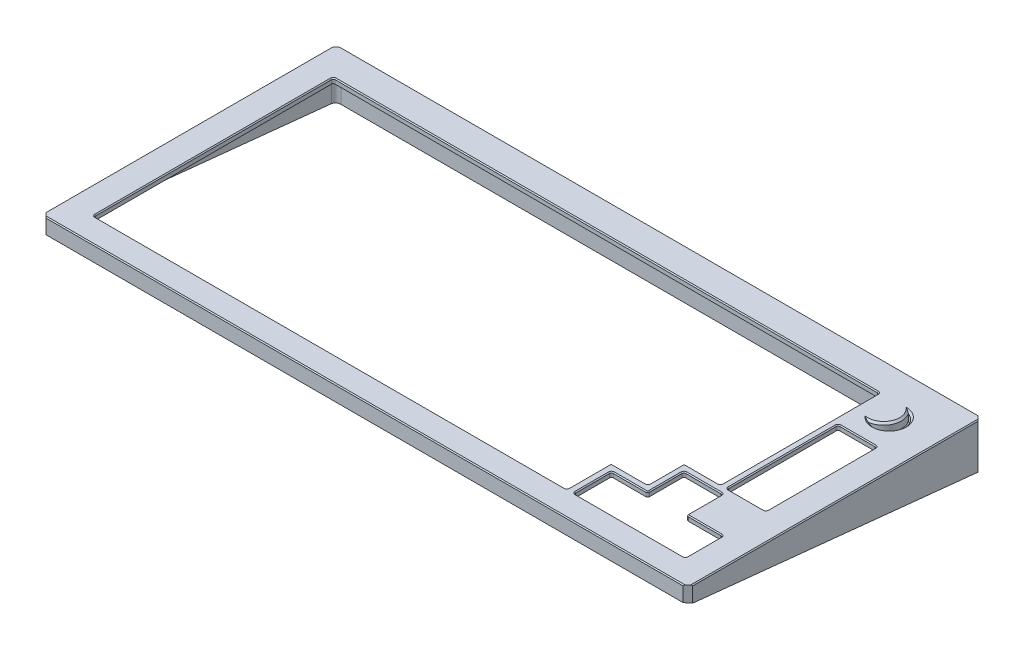
SolidWorks part; units mm, degrees
material "6061-T6 (SS)"
ref_plane "Front Plane" through (0, 0, 0) normal (0, 0, 1) x (1, 0, 0)
ref_plane "Top Plane" through (0, 0, 0) normal (0, 1, 0) x (1, 0, 0)
ref_plane "Right Plane" through (0, 0, 0) normal (1, 0, 0) x (0, 0, -1)
sketch "Sketch1" plane through (0, 0, 0) normal (0, 1, 0) x (1, 0, 0)
  line L0 (-155.4562, -6.3813) -> (-170, -6.3813)
  line L1 (-170, -77.5) -> (170, -77.5)
  line L2 (-170, -77.5) -> (-170, 77.5)
  line L3 (-170, 77.5) -> (170, 77.5)
  line L4 (170, -77.5) -> (170, 77.5)
  line L5 (-170, -77.5) -> (170, 77.5) construction
  line L6 (-170, 77.5) -> (170, -77.5) construction
  line L7 (155.4562, -6.3813) -> (170, -6.3813)
  line L8 (0, 77.5) -> (0, 61.5062)
  line L9 (0, -61.5063) -> (0, -77.5)
  point P0 (0, 0)
  point P12 (0, -59.8446)
  point P15 (0, -62.4563)
  point P16 (155.4563, -6.0337)
  point P17 (170, -3.9033)
  point P18 (-155.4563, -3.3815)
  point P19 (0, -61.5063)
  point P20 (0, 0)
  line B0 (110.1812, 14.1438) -> (123.1812, 14.1438)
  line B1 (109.6812, 0.6437) -> (109.6812, 5.8788)
  line B2 (-155.4563, 60.4062) -> (-155.4563, -6.3813)
  line B3 (-96.8597, 61.5062) -> (-154.3563, 61.5062)
  line B4 (155.4562, -6.3813) -> (155.4562, 36.9899)
  line B5 (31.1843, -61.5063) -> (85.1812, -61.5063)
  line B6 (-77.3157, -40.5052) -> (-77.3157, -53.3062)
  line B7 (23.1843, -40.0052) -> (29.1843, -40.0052)
  line B8 (29.6843, -40.5052) -> (29.6843, -60.0063)
  line B9 (22.6843, -53.3062) -> (22.6843, -40.5053)
  line B10 (-76.8157, -40.0052) -> (-70.8157, -40.0052)
  line B11 (-37.9546, -56.5062) -> (-37.9546, -43.5063)
  line B12 (-102.2522, -56.5063) -> (-102.2522, -43.5063)
  line B13 (-126.0662, -56.5063) -> (-126.0662, -43.5063)
  line B14 (-149.8773, -56.5063) -> (-149.8773, -43.5063)
  line B15 (-92.1046, -57.0063) -> (-101.7522, -57.0063)
  line B16 (-101.7522, -43.0063) -> (-92.1046, -43.0063)
  line B17 (-104.9171, -43.5063) -> (-104.9171, -56.5063)
  line B18 (-105.4171, -57.0063) -> (-125.5662, -57.0063)
  line B19 (-125.5662, -43.0063) -> (-105.4171, -43.0063)
  line B20 (-133.4921, -43.5063) -> (-133.4921, -56.5063)
  line B21 (-133.9921, -57.0063) -> (-149.3773, -57.0063)
  line B22 (-149.3773, -43.0063) -> (-133.9921, -43.0063)
  line B23 (-70.3157, -40.5052) -> (-70.3157, -60.0063)
  line B24 (-17.3157, -57.0062) -> (-37.4546, -57.0062)
  line B25 (-37.4546, -43.0063) -> (-17.3157, -43.0063)
  line B26 (-16.8157, -42.681) -> (-16.8157, -56.5062)
  line B27 (-154.3563, -61.5063) -> (-93.1046, -61.5063)
  line B28 (-68.8157, -61.5063) -> (15.051, -61.5063)
  line B29 (99.0562, -64.3688) -> (153.9562, -64.3688)
  line B30 (16.551, -57.3062) -> (16.551, -60.0062)
  line B31 (86.6812, -57.3063) -> (86.6812, -60.0063)
  line B32 (91.6812, -57.3063) -> (91.6812, -60.0062)
  line B33 (19.051, -54.8062) -> (21.1843, -54.8062)
  line B34 (-83.1046, -54.8062) -> (-78.8157, -54.8062)
  line B35 (93.1812, -61.5062) -> (96.0594, -61.5063)
  line B36 (-155.4563, -6.3813) -> (-155.4563, -60.4063)
  line B37 (155.4562, -6.3813) -> (155.4562, -62.8688)
  line B38 (-88.8597, 61.5062) -> (84.1153, 61.5062)
  line B39 (92.1153, 61.5062) -> (132.2437, 61.5062)
  line B40 (133.7437, 60.0062) -> (133.7437, 39.9899)
  line B41 (135.2437, 38.4899) -> (153.9562, 38.4899)
  line B42 (107.3456, -28.4563) -> (109.3456, -28.4563)
  line B43 (109.8456, -28.9563) -> (109.8456, -32.9563)
  line B44 (109.3456, -33.4563) -> (107.3456, -33.4563)
  line B45 (106.8456, -32.9563) -> (106.8456, -28.9563)
  line B46 (96.4179, 35.6937) -> (96.4179, 33.6938)
  line B47 (103.9179, 33.1937) -> (119.9179, 33.1937)
  line B48 (103.9179, 19.1937) -> (119.9179, 19.1937)
  line B49 (96.9179, 36.1937) -> (102.9179, 36.1937)
  line B50 (96.9179, 16.1937) -> (102.9179, 16.1937)
  line B51 (103.4179, 33.6937) -> (103.4179, 35.6937)
  line B52 (103.4179, 18.6937) -> (103.4179, 16.6937)
  line B53 (127.4179, 35.6937) -> (127.4179, 33.6938)
  line B54 (126.9179, 36.1937) -> (120.9179, 36.1937)
  line B55 (126.9179, 16.1937) -> (120.9179, 16.1937)
  line B56 (120.4179, 33.6937) -> (120.4179, 35.6937)
  line B57 (120.4179, 18.6937) -> (120.4179, 16.6937)
  line B58 (94.0392, -18.9062) -> (94.0392, -21.4062)
  line B59 (101.0392, -18.9063) -> (116.54, -18.9062)
  line B60 (94.5392, -1.9063) -> (100.5392, -1.9062)
  line B61 (94.5392, -21.9062) -> (100.5392, -21.9062)
  line B62 (101.0392, -4.9063) -> (101.0392, -2.4063)
  line B63 (101.0392, -18.9063) -> (101.0392, -21.4062)
  line B64 (124.5392, -21.9062) -> (118.5392, -21.9062)
  line B65 (118.0392, -18.1212) -> (118.0392, -21.4062)
  line B66 (-148.8483, -21.456) -> (-148.8483, -23.4562)
  line B67 (-141.3483, -23.956) -> (-125.3483, -23.956)
  line B68 (-141.3483, -37.9559) -> (-125.3483, -37.9559)
  line B69 (-148.3483, -20.956) -> (-142.3483, -20.956)
  line B70 (-148.3483, -40.9559) -> (-142.3483, -40.9559)
  line B71 (-141.8483, -23.456) -> (-141.8483, -21.456)
  line B72 (-141.8483, -38.4559) -> (-141.8483, -40.4559)
  line B73 (-117.8483, -21.456) -> (-117.8483, -23.4562)
  line B74 (-118.3483, -20.956) -> (-124.3483, -20.956)
  line B75 (-118.3483, -40.9559) -> (-124.3483, -40.9559)
  line B76 (-124.8483, -23.456) -> (-124.8483, -21.456)
  line B77 (-124.8483, -38.4559) -> (-124.8483, -40.4559)
  line B78 (94.0392, -18.9062) -> (91.1338, -18.9062)
  line B79 (112.065, 0.1438) -> (110.1812, 0.1437)
  line B80 (112.065, -4.9063) -> (112.065, 0.1438)
  line B81 (128.0392, 12.8168) -> (128.0392, 6.3788)
  line B82 (128.0392, -11.1832) -> (128.0392, -17.6212)
  line B83 (127.5392, 13.3168) -> (123.6837, 13.3168)
  line B84 (91.1338, -4.9062) -> (94.0392, -4.9062)
  line B85 (126.065, 4.5978) -> (126.065, -9.4022)
  line B86 (90.6338, -5.4062) -> (90.6338, -18.4062)
  line B87 (123.6837, 5.8788) -> (127.5392, 5.8788)
  line B88 (125.0392, -10.6832) -> (127.5392, -10.6832)
  line B89 (126.065, 4.5978) -> (123.6837, 4.5978)
  line B90 (123.6837, 4.5978) -> (123.6837, 5.8788)
  line B91 (125.0392, -10.6832) -> (125.0392, -9.4022)
  line B92 (125.0392, -9.4022) -> (126.065, -9.4022)
  line B93 (118.0392, -18.1212) -> (116.54, -18.1212)
  line B94 (116.54, -18.1212) -> (116.54, -18.9062)
  line B95 (94.0392, -2.4063) -> (94.0392, -4.9062)
  line B96 (125.0392, -21.4063) -> (125.0392, -18.1212)
  line B97 (127.5392, -18.1212) -> (125.0392, -18.1212)
  line B98 (123.6812, 13.6438) -> (123.6837, 13.3168)
  line B99 (101.0392, -4.9063) -> (112.065, -4.9063)
  line B100 (108.0392, 12.8168) -> (108.0392, 6.3788)
  line B101 (108.5392, 13.3168) -> (109.6812, 13.3168)
  line B102 (109.6812, 5.8788) -> (108.5392, 5.8788)
  line B103 (109.6812, 13.3168) -> (109.6812, 13.6438)
  line B104 (95.3937, 19.6937) -> (95.3937, 32.6937)
  line B105 (128.4437, 32.6937) -> (128.4437, 19.6937)
  line B106 (127.4179, 16.6937) -> (127.4179, 18.6938)
  line B107 (127.9179, 19.1938) -> (127.9437, 19.1938)
  line B108 (127.9179, 33.1937) -> (127.9437, 33.1937)
  line B109 (95.8937, 33.1938) -> (95.9179, 33.1938)
  line B110 (96.4179, 16.6937) -> (96.4179, 18.6938)
  line B111 (95.9179, 19.1938) -> (95.8937, 19.1938)
  line B112 (-114.4438, -24.4563) -> (-114.4438, -37.4563)
  line B113 (-117.8483, -40.4559) -> (-117.8483, -38.4563)
  line B114 (-117.3483, -37.9563) -> (-114.9438, -37.9563)
  line B115 (-117.3483, -23.9563) -> (-114.9437, -23.9563)
  line B116 (-149.875, -37.4563) -> (-149.875, -24.4563)
  line B117 (-148.8483, -40.4559) -> (-148.8483, -38.4563)
  line B118 (-149.3483, -37.9563) -> (-149.375, -37.9563)
  line B119 (-149.375, -23.9563) -> (-149.3483, -23.9563)
  line B120 (-84.6046, -40.5052) -> (-84.6046, -53.3062)
  line B121 (-91.6046, -57.5063) -> (-91.6046, -60.0063)
  line B122 (-91.6046, -42.5063) -> (-91.6046, -40.5052)
  line B123 (-91.1046, -40.0052) -> (-85.1046, -40.0052)
  line B124 (-43.7703, -55.5063) -> (-43.7703, -44.5063)
  line B125 (-65.2703, -56.0063) -> (-44.2703, -56.0063)
  line B126 (-65.7703, -44.5063) -> (-65.7703, -55.5063)
  line B127 (-44.2703, -44.0062) -> (-65.2703, -44.0062)
  line B128 (-151.7813, 42.9812) -> (-138.7313, 42.9812)
  line B129 (-138.2313, 43.4812) -> (-138.2313, 56.5312)
  line B130 (-138.7313, 57.0312) -> (-151.7813, 57.0312)
  line B131 (-152.2813, 56.5312) -> (-152.2813, 43.4812)
  line B132 (-127.9688, 42.9812) -> (-114.9188, 42.9812)
  line B133 (-114.4188, 43.4812) -> (-114.4188, 56.5312)
  line B134 (-114.9188, 57.0312) -> (-127.9688, 57.0312)
  line B135 (-128.4688, 56.5312) -> (-128.4688, 43.4812)
  line B136 (-70.8188, 42.9812) -> (-57.7688, 42.9812)
  line B137 (-57.2688, 43.4812) -> (-57.2688, 56.5312)
  line B138 (-57.7688, 57.0312) -> (-70.8188, 57.0312)
  line B139 (-71.3188, 56.5312) -> (-71.3188, 43.4812)
  line B140 (-47.0063, 42.9812) -> (-33.9563, 42.9812)
  line B141 (-33.4563, 43.4812) -> (-33.4563, 56.5312)
  line B142 (-33.9563, 57.0312) -> (-47.0063, 57.0312)
  line B143 (-47.5063, 56.5312) -> (-47.5063, 43.4812)
  line B144 (-27.9563, 42.9812) -> (-14.9063, 42.9812)
  line B145 (-14.4063, 43.4812) -> (-14.4063, 56.5312)
  line B146 (-14.9063, 57.0312) -> (-27.9563, 57.0312)
  line B147 (-28.4563, 56.5312) -> (-28.4563, 43.4812)
  line B148 (-8.9063, 42.9812) -> (4.1437, 42.9812)
  line B149 (4.6437, 43.4812) -> (4.6437, 56.5312)
  line B150 (4.1437, 57.0312) -> (-8.9063, 57.0312)
  line B151 (-9.4063, 56.5312) -> (-9.4063, 43.4812)
  line B152 (10.1437, 42.9812) -> (23.1937, 42.9812)
  line B153 (23.6937, 43.4812) -> (23.6937, 56.5312)
  line B154 (23.1937, 57.0312) -> (10.1437, 57.0312)
  line B155 (9.6437, 56.5312) -> (9.6437, 43.4812)
  line B156 (33.9562, 42.9812) -> (47.0062, 42.9812)
  line B157 (47.5062, 43.4812) -> (47.5062, 56.5312)
  line B158 (47.0062, 57.0312) -> (33.9562, 57.0312)
  line B159 (33.4562, 56.5312) -> (33.4562, 43.4812)
  line B160 (53.0062, 42.9812) -> (66.0562, 42.9812)
  line B161 (66.5562, 43.4812) -> (66.5562, 56.5312)
  line B162 (66.0562, 57.0312) -> (53.0062, 57.0312)
  line B163 (52.5062, 56.5312) -> (52.5062, 43.4812)
  line B164 (114.9187, 42.9812) -> (127.9687, 42.9812)
  line B165 (128.4687, 43.4812) -> (128.4687, 56.5312)
  line B166 (127.9687, 57.0312) -> (114.9187, 57.0312)
  line B167 (114.4187, 56.5312) -> (114.4187, 43.4812)
  line B168 (138.7312, 19.1687) -> (151.7812, 19.1687)
  line B169 (152.2812, 19.6687) -> (152.2812, 32.7187)
  line B170 (151.7812, 33.2187) -> (138.7312, 33.2187)
  line B171 (138.2312, 32.7187) -> (138.2312, 19.6687)
  line B172 (119.6812, -42.7438) -> (132.7312, -42.7438)
  line B173 (133.2312, -42.2438) -> (133.2312, -29.1938)
  line B174 (132.7312, -28.6938) -> (119.6812, -28.6938)
  line B175 (119.1812, -29.1938) -> (119.1812, -42.2438)
  line B176 (138.7312, -61.7938) -> (151.7812, -61.7938)
  line B177 (152.2812, -61.2938) -> (152.2812, -48.2438)
  line B178 (151.7812, -47.7438) -> (138.7312, -47.7438)
  line B179 (138.2312, -48.2438) -> (138.2312, -61.2938)
  line B180 (119.6812, -61.7938) -> (132.7312, -61.7938)
  line B181 (133.2312, -61.2938) -> (133.2312, -48.2438)
  line B182 (132.7312, -47.7438) -> (119.6812, -47.7438)
  line B183 (119.1812, -48.2438) -> (119.1812, -61.2938)
  line B184 (100.6312, -61.7938) -> (113.6812, -61.7938)
  line B185 (114.1812, -61.2938) -> (114.1812, -48.2438)
  line B186 (113.6812, -47.7438) -> (100.6312, -47.7438)
  line B187 (100.1312, -48.2438) -> (100.1312, -61.2938)
  line B188 (72.0562, -57.0313) -> (85.1062, -57.0313)
  line B189 (85.6062, -56.5313) -> (85.6062, -43.4813)
  line B190 (85.1062, -42.9813) -> (72.0562, -42.9813)
  line B191 (71.5562, -43.4813) -> (71.5562, -56.5313)
  line B192 (43.4812, -57.0313) -> (56.5312, -57.0313)
  line B193 (57.0312, -56.5313) -> (57.0312, -43.4813)
  line B194 (56.5312, -42.9813) -> (43.4812, -42.9813)
  line B195 (42.9812, -43.4813) -> (42.9812, -56.5313)
  line B196 (88.725, -37.9813) -> (101.775, -37.9813)
  line B197 (102.275, -37.4813) -> (102.275, -24.4313)
  line B198 (101.775, -23.9313) -> (88.725, -23.9313)
  line B199 (88.225, -24.4313) -> (88.225, -37.4813)
  line B200 (62.5312, -37.9813) -> (75.5812, -37.9813)
  line B201 (76.0812, -37.4813) -> (76.0812, -24.4313)
  line B202 (75.5812, -23.9313) -> (62.5312, -23.9313)
  line B203 (62.0312, -24.4313) -> (62.0312, -37.4813)
  line B204 (43.4812, -37.9813) -> (56.5312, -37.9813)
  line B205 (57.0312, -37.4813) -> (57.0312, -24.4313)
  line B206 (56.5312, -23.9313) -> (43.4812, -23.9313)
  line B207 (42.9812, -24.4313) -> (42.9812, -37.4813)
  line B208 (24.4312, -37.9813) -> (37.4812, -37.9813)
  line B209 (37.9812, -37.4813) -> (37.9812, -24.4313)
  line B210 (37.4812, -23.9313) -> (24.4312, -23.9313)
  line B211 (23.9312, -24.4313) -> (23.9312, -37.4813)
  line B212 (5.3812, -37.9813) -> (18.4312, -37.9813)
  line B213 (18.9312, -37.4813) -> (18.9312, -24.4313)
  line B214 (18.4312, -23.9313) -> (5.3812, -23.9313)
  line B215 (4.8812, -24.4313) -> (4.8812, -37.4813)
  line B216 (-13.6688, -37.9813) -> (-0.6188, -37.9813)
  line B217 (-0.1188, -37.4813) -> (-0.1188, -24.4313)
  line B218 (-0.6188, -23.9313) -> (-13.6688, -23.9313)
  line B219 (-14.1688, -24.4313) -> (-14.1688, -37.4813)
  line B220 (-32.7188, -37.9813) -> (-19.6688, -37.9813)
  line B221 (-19.1688, -37.4813) -> (-19.1688, -24.4313)
  line B222 (-19.6688, -23.9313) -> (-32.7188, -23.9313)
  line B223 (-33.2188, -24.4313) -> (-33.2188, -37.4813)
  line B224 (-51.7688, -37.9813) -> (-38.7188, -37.9813)
  line B225 (-38.2188, -37.4813) -> (-38.2188, -24.4313)
  line B226 (-38.7188, -23.9313) -> (-51.7688, -23.9313)
  line B227 (-52.2688, -24.4313) -> (-52.2688, -37.4813)
  line B228 (-70.8188, -37.9813) -> (-57.7688, -37.9813)
  line B229 (-57.2688, -37.4813) -> (-57.2688, -24.4313)
  line B230 (-57.7688, -23.9313) -> (-70.8188, -23.9313)
  line B231 (-71.3188, -24.4313) -> (-71.3188, -37.4813)
  line B232 (-89.8688, -37.9813) -> (-76.8188, -37.9813)
  line B233 (-76.3188, -37.4813) -> (-76.3188, -24.4313)
  line B234 (-76.8188, -23.9313) -> (-89.8688, -23.9313)
  line B235 (-90.3688, -24.4313) -> (-90.3688, -37.4813)
  line B236 (-108.9188, -37.9813) -> (-95.8688, -37.9813)
  line B237 (-95.3688, -37.4813) -> (-95.3688, -24.4313)
  line B238 (-95.8688, -23.9313) -> (-108.9188, -23.9313)
  line B239 (-109.4188, -24.4313) -> (-109.4188, -37.4813)
  line B240 (-118.4438, -18.9313) -> (-105.3938, -18.9313)
  line B241 (-104.8938, -18.4313) -> (-104.8938, -5.3813)
  line B242 (-105.3938, -4.8813) -> (-118.4438, -4.8813)
  line B243 (-118.9438, -5.3813) -> (-118.9438, -18.4313)
  line B244 (-99.3938, -18.9313) -> (-86.3438, -18.9313)
  line B245 (-85.8438, -18.4313) -> (-85.8438, -5.3813)
  line B246 (-86.3438, -4.8813) -> (-99.3938, -4.8813)
  line B247 (-99.8938, -5.3813) -> (-99.8938, -18.4313)
  line B248 (-80.3438, -18.9313) -> (-67.2938, -18.9313)
  line B249 (-66.7938, -18.4313) -> (-66.7938, -5.3813)
  line B250 (-67.2938, -4.8813) -> (-80.3438, -4.8813)
  line B251 (-80.8438, -5.3813) -> (-80.8438, -18.4313)
  line B252 (-61.2938, -18.9313) -> (-48.2438, -18.9313)
  line B253 (-47.7438, -18.4313) -> (-47.7438, -5.3813)
  line B254 (-48.2438, -4.8813) -> (-61.2938, -4.8813)
  line B255 (-61.7938, -5.3813) -> (-61.7938, -18.4313)
  line B256 (-42.2438, -18.9313) -> (-29.1938, -18.9313)
  line B257 (-28.6938, -18.4313) -> (-28.6938, -5.3813)
  line B258 (-29.1938, -4.8813) -> (-42.2438, -4.8813)
  line B259 (-42.7438, -5.3813) -> (-42.7438, -18.4313)
  line B260 (-23.1938, -18.9313) -> (-10.1438, -18.9313)
  line B261 (-9.6438, -18.4313) -> (-9.6438, -5.3813)
  line B262 (-10.1438, -4.8813) -> (-23.1938, -4.8813)
  line B263 (-23.6938, -5.3813) -> (-23.6938, -18.4313)
  line B264 (-4.1438, -18.9313) -> (8.9062, -18.9313)
  line B265 (9.4062, -18.4313) -> (9.4062, -5.3813)
  line B266 (8.9062, -4.8813) -> (-4.1438, -4.8813)
  line B267 (-4.6438, -5.3813) -> (-4.6438, -18.4313)
  line B268 (14.9062, -18.9313) -> (27.9562, -18.9313)
  line B269 (28.4562, -18.4313) -> (28.4562, -5.3813)
  line B270 (27.9562, -4.8813) -> (14.9062, -4.8813)
  line B271 (14.4062, -5.3813) -> (14.4062, -18.4313)
  line B272 (33.9562, -18.9313) -> (47.0062, -18.9313)
  line B273 (47.5062, -18.4313) -> (47.5062, -5.3813)
  line B274 (47.0062, -4.8813) -> (33.9562, -4.8813)
  line B275 (33.4562, -5.3813) -> (33.4562, -18.4313)
  line B276 (53.0062, -18.9313) -> (66.0562, -18.9313)
  line B277 (66.5562, -18.4313) -> (66.5562, -5.3813)
  line B278 (66.0562, -4.8813) -> (53.0062, -4.8813)
  line B279 (52.5062, -5.3813) -> (52.5062, -18.4313)
  line B280 (72.0562, -18.9313) -> (85.1062, -18.9313)
  line B281 (85.6062, -18.4313) -> (85.6062, -5.3813)
  line B282 (85.1062, -4.8813) -> (72.0562, -4.8813)
  line B283 (71.5562, -5.3813) -> (71.5562, -18.4313)
  line B284 (-147.0188, 0.1187) -> (-133.9688, 0.1187)
  line B285 (-133.4688, 0.6187) -> (-133.4688, 13.6687)
  line B286 (-133.9688, 14.1687) -> (-147.0188, 14.1687)
  line B287 (-147.5188, 13.6687) -> (-147.5188, 0.6187)
  line B288 (-151.7813, 19.1687) -> (-138.7313, 19.1687)
  line B289 (-138.2313, 19.6687) -> (-138.2313, 32.7187)
  line B290 (-138.7313, 33.2187) -> (-151.7813, 33.2187)
  line B291 (-152.2813, 32.7187) -> (-152.2813, 19.6687)
  line B292 (-132.7313, 19.1687) -> (-119.6813, 19.1687)
  line B293 (-119.1813, 19.6687) -> (-119.1813, 32.7187)
  line B294 (-119.6813, 33.2187) -> (-132.7313, 33.2187)
  line B295 (-133.2313, 32.7187) -> (-133.2313, 19.6687)
  line B296 (-113.6813, 19.1687) -> (-100.6313, 19.1687)
  line B297 (-100.1313, 19.6687) -> (-100.1313, 32.7187)
  line B298 (-100.6313, 33.2187) -> (-113.6813, 33.2187)
  line B299 (-114.1813, 32.7187) -> (-114.1813, 19.6687)
  line B300 (-94.6313, 19.1687) -> (-81.5813, 19.1687)
  line B301 (-81.0813, 19.6687) -> (-81.0813, 32.7187)
  line B302 (-81.5813, 33.2187) -> (-94.6313, 33.2187)
  line B303 (-95.1313, 32.7187) -> (-95.1313, 19.6687)
  line B304 (-75.5813, 19.1687) -> (-62.5313, 19.1687)
  line B305 (-62.0313, 19.6687) -> (-62.0313, 32.7187)
  line B306 (-62.5313, 33.2187) -> (-75.5813, 33.2187)
  line B307 (-76.0813, 32.7187) -> (-76.0813, 19.6687)
  line B308 (-56.5313, 19.1687) -> (-43.4813, 19.1687)
  line B309 (-42.9813, 19.6687) -> (-42.9813, 32.7187)
  line B310 (-43.4813, 33.2187) -> (-56.5313, 33.2187)
  line B311 (-57.0313, 32.7187) -> (-57.0313, 19.6687)
  line B312 (-37.4813, 19.1687) -> (-24.4313, 19.1687)
  line B313 (-23.9313, 19.6687) -> (-23.9313, 32.7187)
  line B314 (-24.4313, 33.2187) -> (-37.4813, 33.2187)
  line B315 (-37.9813, 32.7187) -> (-37.9813, 19.6687)
  line B316 (-18.4313, 19.1687) -> (-5.3813, 19.1687)
  line B317 (-4.8813, 19.6687) -> (-4.8813, 32.7187)
  line B318 (-5.3813, 33.2187) -> (-18.4313, 33.2187)
  line B319 (-18.9313, 32.7187) -> (-18.9313, 19.6687)
  line B320 (0.6187, 19.1687) -> (13.6687, 19.1687)
  line B321 (14.1687, 19.6687) -> (14.1687, 32.7187)
  line B322 (13.6687, 33.2187) -> (0.6187, 33.2187)
  line B323 (0.1187, 32.7187) -> (0.1187, 19.6687)
  line B324 (19.6687, 19.1687) -> (32.7187, 19.1687)
  line B325 (33.2187, 19.6687) -> (33.2187, 32.7188)
  line B326 (32.7187, 33.2188) -> (19.6687, 33.2188)
  line B327 (19.1687, 32.7188) -> (19.1687, 19.6687)
  line B328 (38.7187, 19.1687) -> (51.7687, 19.1687)
  line B329 (52.2687, 19.6687) -> (52.2687, 32.7188)
  line B330 (51.7687, 33.2188) -> (38.7187, 33.2188)
  line B331 (38.2187, 32.7188) -> (38.2187, 19.6687)
  line B332 (57.7687, 19.1687) -> (70.8187, 19.1687)
  line B333 (71.3187, 19.6687) -> (71.3187, 32.7187)
  line B334 (70.8187, 33.2187) -> (57.7687, 33.2187)
  line B335 (57.2687, 32.7187) -> (57.2687, 19.6687)
  line B336 (76.8187, 19.1687) -> (89.8687, 19.1687)
  line B337 (90.3687, 19.6687) -> (90.3687, 32.7187)
  line B338 (89.8687, 33.2187) -> (76.8187, 33.2187)
  line B339 (76.3187, 32.7187) -> (76.3187, 19.6687)
  line B340 (-123.2063, 0.1187) -> (-110.1563, 0.1187)
  line B341 (-109.6563, 0.6187) -> (-109.6563, 13.6687)
  line B342 (-110.1563, 14.1687) -> (-123.2063, 14.1687)
  line B343 (-123.7063, 13.6687) -> (-123.7063, 0.6187)
  line B344 (-104.1563, 0.1187) -> (-91.1063, 0.1187)
  line B345 (-90.6063, 0.6187) -> (-90.6063, 13.6687)
  line B346 (-91.1063, 14.1687) -> (-104.1563, 14.1687)
  line B347 (-104.6563, 13.6687) -> (-104.6563, 0.6187)
  line B348 (-85.1063, 0.1187) -> (-72.0563, 0.1187)
  line B349 (-71.5563, 0.6187) -> (-71.5563, 13.6687)
  line B350 (-72.0563, 14.1687) -> (-85.1063, 14.1687)
  line B351 (-85.6063, 13.6687) -> (-85.6063, 0.6187)
  line B352 (-66.0563, 0.1187) -> (-53.0063, 0.1187)
  line B353 (-52.5063, 0.6187) -> (-52.5063, 13.6687)
  line B354 (-53.0063, 14.1687) -> (-66.0563, 14.1687)
  line B355 (-66.5563, 13.6687) -> (-66.5563, 0.6187)
  line B356 (-47.0063, 0.1187) -> (-33.9563, 0.1187)
  line B357 (-33.4563, 0.6187) -> (-33.4563, 13.6687)
  line B358 (-33.9563, 14.1687) -> (-47.0063, 14.1687)
  line B359 (-47.5063, 13.6687) -> (-47.5063, 0.6187)
  line B360 (-27.9563, 0.1187) -> (-14.9063, 0.1187)
  line B361 (-14.4063, 0.6187) -> (-14.4063, 13.6687)
  line B362 (-14.9063, 14.1687) -> (-27.9563, 14.1687)
  line B363 (-28.4563, 13.6687) -> (-28.4563, 0.6187)
  line B364 (-8.9063, 0.1187) -> (4.1437, 0.1187)
  line B365 (4.6437, 0.6187) -> (4.6437, 13.6687)
  line B366 (4.1437, 14.1687) -> (-8.9063, 14.1687)
  line B367 (-9.4063, 13.6687) -> (-9.4063, 0.6187)
  line B368 (10.1437, 0.1187) -> (23.1937, 0.1187)
  line B369 (23.6937, 0.6187) -> (23.6937, 13.6687)
  line B370 (23.1937, 14.1687) -> (10.1437, 14.1687)
  line B371 (9.6437, 13.6687) -> (9.6437, 0.6187)
  line B372 (29.1937, 0.1187) -> (42.2437, 0.1187)
  line B373 (42.7437, 0.6187) -> (42.7437, 13.6687)
  line B374 (42.2437, 14.1687) -> (29.1937, 14.1687)
  line B375 (28.6937, 13.6687) -> (28.6937, 0.6187)
  line B376 (48.2437, 0.1187) -> (61.2937, 0.1187)
  line B377 (61.7937, 0.6187) -> (61.7937, 13.6687)
  line B378 (61.2937, 14.1687) -> (48.2437, 14.1687)
  line B379 (47.7437, 13.6687) -> (47.7437, 0.6187)
  line B380 (67.2937, 0.1187) -> (80.3437, 0.1187)
  line B381 (80.8437, 0.6187) -> (80.8437, 13.6687)
  line B382 (80.3437, 14.1687) -> (67.2937, 14.1687)
  line B383 (66.7937, 13.6687) -> (66.7937, 0.6187)
  line B384 (86.3437, 0.1187) -> (99.3937, 0.1187)
  line B385 (99.8937, 0.6187) -> (99.8937, 13.6687)
  line B386 (99.3937, 14.1687) -> (86.3437, 14.1687)
  line B387 (85.8437, 13.6687) -> (85.8437, 0.6187)
  line B388 (138.7312, 0.1188) -> (151.7812, 0.1188)
  line B389 (152.2812, 0.6188) -> (152.2812, 13.6688)
  line B390 (151.7812, 14.1688) -> (138.7312, 14.1688)
  line B391 (138.2312, 13.6688) -> (138.2312, 0.6188)
  line B392 (138.7562, -4.8813) -> (151.8062, -4.8813)
  line B393 (138.2312, -18.4063) -> (138.2312, -5.4063)
  line B394 (151.7562, -18.9313) -> (138.7562, -18.9313)
  line B395 (152.2812, -5.3563) -> (152.2812, -18.4063)
  line B396 (-131.6125, -18.9563) -> (-149.375, -18.9563)
  line B397 (-131.0625, -5.4063) -> (-131.0625, -18.4063)
  line B398 (-149.375, -4.8563) -> (-131.6125, -4.8563)
  line B399 (-149.925, -18.4063) -> (-149.925, -5.4063)
  line B400 (72.0562, 42.9812) -> (85.1062, 42.9812)
  line B401 (85.6062, 43.4812) -> (85.6062, 56.5312)
  line B402 (85.1062, 57.0312) -> (72.0562, 57.0312)
  line B403 (71.5562, 56.5312) -> (71.5562, 43.4812)
  line B404 (91.1062, 42.9812) -> (104.1563, 42.9812)
  line B405 (104.6563, 43.4812) -> (104.6563, 56.5312)
  line B406 (104.1563, 57.0312) -> (91.1062, 57.0312)
  line B407 (90.6062, 56.5312) -> (90.6062, 43.4812)
  line B408 (-108.9188, 42.9812) -> (-95.8688, 42.9812)
  line B409 (-95.3688, 43.4812) -> (-95.3688, 56.5312)
  line B410 (-95.8688, 57.0312) -> (-108.9188, 57.0312)
  line B411 (-109.4188, 56.5312) -> (-109.4188, 43.4812)
  line B412 (-89.8688, 42.9812) -> (-76.8188, 42.9812)
  line B413 (-76.3188, 43.4812) -> (-76.3188, 56.5312)
  line B414 (-76.8188, 57.0312) -> (-89.8688, 57.0312)
  line B415 (-90.3688, 56.5312) -> (-90.3688, 43.4812)
  line B416 (-96.8597, 61.5062) -> (-88.8597, 61.5062)
  line B417 (84.1153, 61.5062) -> (92.1153, 61.5062)
  arc B418 (155.4562, 36.9899) -> (153.9562, 38.4899) centre (153.9562, 36.9899) ccw
  arc B419 (153.9562, -64.3688) -> (155.4562, -62.8688) centre (153.9562, -62.8688) ccw
  arc B420 (29.6843, -60.0063) -> (31.1843, -61.5063) centre (31.1843, -60.0063) ccw
  arc B421 (109.6812, 0.6437) -> (110.1812, 0.1437) centre (110.1812, 0.6437) ccw
  arc B422 (123.6812, 13.6438) -> (123.1812, 14.1438) centre (123.1812, 13.6438) ccw
  arc B423 (110.1812, 14.1438) -> (109.6812, 13.6438) centre (110.1812, 13.6438) ccw
  arc B424 (-155.4563, -60.4063) -> (-154.3563, -61.5063) centre (-154.3563, -60.4063) ccw
  arc B425 (-154.3563, 61.5062) -> (-155.4563, 60.4062) centre (-154.3563, 60.4062) ccw
  arc B426 (-78.8157, -54.8062) -> (-77.3157, -53.3062) centre (-78.8157, -53.3062) ccw
  arc B427 (29.6843, -40.5052) -> (29.1843, -40.0052) centre (29.1843, -40.5052) ccw
  arc B428 (23.1843, -40.0052) -> (22.6843, -40.5053) centre (23.1843, -40.5052) ccw
  arc B429 (21.1843, -54.8062) -> (22.6843, -53.3062) centre (21.1843, -53.3062) ccw
  arc B430 (-76.8157, -40.0052) -> (-77.3157, -40.5052) centre (-76.8157, -40.5052) ccw
  arc B431 (-37.9546, -56.5062) -> (-37.4546, -57.0062) centre (-37.4546, -56.5062) ccw
  arc B432 (-70.3157, -40.5052) -> (-70.8157, -40.0052) centre (-70.8157, -40.5052) ccw
  arc B433 (-125.5662, -43.0063) -> (-126.0662, -43.5063) centre (-125.5662, -43.5063) ccw
  arc B434 (-149.3773, -43.0063) -> (-149.8773, -43.5063) centre (-149.3773, -43.5063) ccw
  arc B435 (-102.2522, -56.5063) -> (-101.7522, -57.0063) centre (-101.7522, -56.5063) ccw
  arc B436 (-101.7522, -43.0063) -> (-102.2522, -43.5063) centre (-101.7522, -43.5063) ccw
  arc B437 (-126.0662, -56.5063) -> (-125.5662, -57.0063) centre (-125.5662, -56.5063) ccw
  arc B438 (-105.4171, -57.0063) -> (-104.9171, -56.5063) centre (-105.4171, -56.5063) ccw
  arc B439 (-104.9171, -43.5063) -> (-105.4171, -43.0063) centre (-105.4171, -43.5063) ccw
  arc B440 (-133.9921, -57.0063) -> (-133.4921, -56.5063) centre (-133.9921, -56.5063) ccw
  arc B441 (-149.8773, -56.5063) -> (-149.3773, -57.0063) centre (-149.3773, -56.5063) ccw
  arc B442 (-133.4921, -43.5063) -> (-133.9921, -43.0063) centre (-133.9921, -43.5063) ccw
  arc B443 (-37.4546, -43.0063) -> (-37.9546, -43.5063) centre (-37.4546, -43.5063) ccw
  arc B444 (-17.3157, -57.0062) -> (-16.8157, -56.5062) centre (-17.3157, -56.5062) ccw
  arc B445 (-16.8157, -42.681) -> (-17.3157, -43.0063) centre (-16.8468, -43.18) ccw
  arc B446 (-70.3157, -60.0063) -> (-68.8157, -61.5063) centre (-68.8157, -60.0063) ccw
  arc B447 (97.5578, -62.9375) -> (99.0562, -64.3688) centre (99.0562, -62.8688) ccw
  arc B448 (97.5578, -62.9375) -> (96.0594, -61.5063) centre (96.0594, -63.0063) ccw
  arc B449 (15.051, -61.5063) -> (16.551, -60.0062) centre (15.051, -60.0063) ccw
  arc B450 (91.6812, -60.0062) -> (93.1812, -61.5062) centre (93.1812, -60.0062) ccw
  arc B451 (85.1812, -61.5063) -> (86.6812, -60.0063) centre (85.1812, -60.0063) ccw
  arc B452 (91.6812, -57.3063) -> (86.6812, -57.3063) centre (89.1812, -57.3063) ccw
  arc B453 (19.051, -54.8062) -> (16.551, -57.3062) centre (19.051, -57.3062) ccw
  arc B454 (133.7437, 60.0062) -> (132.2437, 61.5062) centre (132.2437, 60.0062) ccw
  arc B455 (133.7437, 39.9899) -> (135.2437, 38.4899) centre (135.2437, 39.9899) ccw
  arc B456 (107.3456, -28.4563) -> (106.8456, -28.9563) centre (107.3456, -28.9563) ccw
  arc B457 (109.8456, -28.9563) -> (109.3456, -28.4563) centre (109.3456, -28.9563) ccw
  arc B458 (109.3456, -33.4563) -> (109.8456, -32.9563) centre (109.3456, -32.9563) ccw
  arc B459 (106.8456, -32.9563) -> (107.3456, -33.4563) centre (107.3456, -32.9563) ccw
  arc B460 (95.9179, 33.1938) -> (96.4179, 33.6938) centre (95.9179, 33.6938) ccw
  arc B461 (103.4179, 33.6937) -> (103.9179, 33.1937) centre (103.9179, 33.6937) ccw
  arc B462 (96.9179, 36.1937) -> (96.4179, 35.6937) centre (96.9179, 35.6937) ccw
  arc B463 (96.4179, 16.6937) -> (96.9179, 16.1937) centre (96.9179, 16.6937) ccw
  arc B464 (103.4179, 35.6937) -> (102.9179, 36.1937) centre (102.9179, 35.6937) ccw
  arc B465 (103.9179, 19.1937) -> (103.4179, 18.6937) centre (103.9179, 18.6937) ccw
  arc B466 (102.9179, 16.1937) -> (103.4179, 16.6937) centre (102.9179, 16.6937) ccw
  arc B467 (119.9179, 33.1937) -> (120.4179, 33.6937) centre (119.9179, 33.6937) ccw
  arc B468 (127.4179, 35.6937) -> (126.9179, 36.1937) centre (126.9179, 35.6937) ccw
  arc B469 (126.9179, 16.1937) -> (127.4179, 16.6937) centre (126.9179, 16.6937) ccw
  arc B470 (120.9179, 36.1937) -> (120.4179, 35.6937) centre (120.9179, 35.6937) ccw
  arc B471 (120.4179, 18.6937) -> (119.9179, 19.1937) centre (119.9179, 18.6937) ccw
  arc B472 (120.4179, 16.6937) -> (120.9179, 16.1937) centre (120.9179, 16.6937) ccw
  arc B473 (94.5392, -1.9063) -> (94.0392, -2.4063) centre (94.5392, -2.4063) ccw
  arc B474 (94.0392, -21.4062) -> (94.5392, -21.9062) centre (94.5392, -21.4062) ccw
  arc B475 (101.0392, -2.4063) -> (100.5392, -1.9062) centre (100.5392, -2.4062) ccw
  arc B476 (100.5392, -21.9062) -> (101.0392, -21.4062) centre (100.5392, -21.4062) ccw
  arc B477 (124.5392, -21.9062) -> (125.0392, -21.4063) centre (124.5392, -21.4062) ccw
  arc B478 (118.0392, -21.4062) -> (118.5392, -21.9062) centre (118.5392, -21.4062) ccw
  arc B479 (-149.3483, -23.9563) -> (-148.8483, -23.4562) centre (-149.3483, -23.4563) ccw
  arc B480 (-141.8483, -23.456) -> (-141.3483, -23.956) centre (-141.3483, -23.456) ccw
  arc B481 (-148.3483, -20.956) -> (-148.8483, -21.456) centre (-148.3483, -21.456) ccw
  arc B482 (-148.8483, -40.4559) -> (-148.3483, -40.9559) centre (-148.3483, -40.4559) ccw
  arc B483 (-141.8483, -21.456) -> (-142.3483, -20.956) centre (-142.3483, -21.456) ccw
  arc B484 (-141.3483, -37.9559) -> (-141.8483, -38.4559) centre (-141.3483, -38.4559) ccw
  arc B485 (-142.3483, -40.9559) -> (-141.8483, -40.4559) centre (-142.3483, -40.4559) ccw
  arc B486 (-125.3483, -23.956) -> (-124.8483, -23.456) centre (-125.3483, -23.456) ccw
  arc B487 (-117.8483, -21.456) -> (-118.3483, -20.956) centre (-118.3483, -21.456) ccw
  arc B488 (-118.3483, -40.9559) -> (-117.8483, -40.4559) centre (-118.3483, -40.4559) ccw
  arc B489 (-124.3483, -20.956) -> (-124.8483, -21.456) centre (-124.3483, -21.456) ccw
  arc B490 (-124.8483, -38.4559) -> (-125.3483, -37.9559) centre (-125.3483, -38.4559) ccw
  arc B491 (-124.8483, -40.4559) -> (-124.3483, -40.9559) centre (-124.3483, -40.4559) ccw
  arc B492 (127.5392, -18.1212) -> (128.0392, -17.6212) centre (127.5392, -17.6212) ccw
  arc B493 (128.0392, 12.8168) -> (127.5392, 13.3168) centre (127.5392, 12.8168) ccw
  arc B494 (128.0392, -11.1832) -> (127.5392, -10.6832) centre (127.5392, -11.1832) ccw
  arc B495 (127.5392, 5.8788) -> (128.0392, 6.3788) centre (127.5392, 6.3788) ccw
  arc B496 (108.5392, 13.3168) -> (108.0392, 12.8168) centre (108.5392, 12.8168) ccw
  arc B497 (108.0392, 6.3788) -> (108.5392, 5.8788) centre (108.5392, 6.3788) ccw
  arc B498 (95.3937, 19.6937) -> (95.8937, 19.1938) centre (95.8937, 19.6938) ccw
  arc B499 (95.8937, 33.1938) -> (95.3937, 32.6937) centre (95.8937, 32.6937) ccw
  arc B500 (127.9437, 19.1938) -> (128.4437, 19.6937) centre (127.9437, 19.6937) ccw
  arc B501 (128.4437, 32.6937) -> (127.9437, 33.1937) centre (127.9437, 32.6938) ccw
  arc B502 (127.9179, 19.1938) -> (127.4179, 18.6938) centre (127.9179, 18.6938) ccw
  arc B503 (127.4179, 33.6938) -> (127.9179, 33.1937) centre (127.9179, 33.6937) ccw
  arc B504 (96.4179, 18.6938) -> (95.9179, 19.1938) centre (95.9179, 18.6938) ccw
  arc B505 (-114.9438, -37.9563) -> (-114.4438, -37.4563) centre (-114.9438, -37.4563) ccw
  arc B506 (-114.4438, -24.4563) -> (-114.9437, -23.9563) centre (-114.9438, -24.4563) ccw
  arc B507 (-117.3483, -37.9563) -> (-117.8483, -38.4563) centre (-117.3483, -38.4563) ccw
  arc B508 (-117.8483, -23.4562) -> (-117.3483, -23.9563) centre (-117.3483, -23.4563) ccw
  arc B509 (-149.875, -37.4563) -> (-149.375, -37.9563) centre (-149.375, -37.4563) ccw
  arc B510 (-149.375, -23.9563) -> (-149.875, -24.4563) centre (-149.375, -24.4563) ccw
  arc B511 (-148.8483, -38.4563) -> (-149.3483, -37.9563) centre (-149.3483, -38.4563) ccw
  arc B512 (-91.6046, -57.5063) -> (-92.1046, -57.0063) centre (-92.1046, -57.5063) ccw
  arc B513 (-92.1046, -43.0063) -> (-91.6046, -42.5063) centre (-92.1046, -42.5063) ccw
  arc B514 (-91.1046, -40.0052) -> (-91.6046, -40.5052) centre (-91.1046, -40.5052) ccw
  arc B515 (-84.6046, -40.5052) -> (-85.1046, -40.0052) centre (-85.1046, -40.5052) ccw
  arc B516 (-93.1046, -61.5063) -> (-91.6046, -60.0063) centre (-93.1046, -60.0063) ccw
  arc B517 (-84.6046, -53.3062) -> (-83.1046, -54.8062) centre (-83.1046, -53.3062) ccw
  arc B518 (91.1338, -4.9062) -> (90.6338, -5.4062) centre (91.1338, -5.4062) ccw
  arc B519 (90.6338, -18.4062) -> (91.1338, -18.9062) centre (91.1338, -18.4062) ccw
  arc B520 (-44.2703, -56.0063) -> (-43.7703, -55.5063) centre (-44.2703, -55.5063) ccw
  arc B521 (-65.7703, -55.5063) -> (-65.2703, -56.0063) centre (-65.2703, -55.5063) ccw
  arc B522 (-65.2703, -44.0062) -> (-65.7703, -44.5063) centre (-65.2703, -44.5063) ccw
  arc B523 (-43.7703, -44.5063) -> (-44.2703, -44.0062) centre (-44.2703, -44.5062) ccw
  circle B524 centre (-3.275, -49.5936) radius 6.0649
  circle B525 centre (2.3706, -49.5936) radius 6.0649
  circle B526 centre (-3.275, -49.5936) radius 7.3149
  circle B527 centre (2.3706, -49.5936) radius 7.3149
  arc B528 (138.7562, -4.8813) -> (138.2312, -5.4063) centre (138.7562, -5.4063) ccw
  arc B529 (138.2312, -18.4063) -> (138.7562, -18.9313) centre (138.7562, -18.4063) ccw
  arc B530 (151.7562, -18.9313) -> (152.2812, -18.4063) centre (151.7562, -18.4063) ccw
  arc B531 (152.2812, -5.3563) -> (151.8062, -4.8813) centre (151.8062, -5.3563) ccw
  arc B532 (-149.925, -18.4063) -> (-149.375, -18.9563) centre (-149.375, -18.4063) ccw
  arc B533 (-131.6125, -18.9563) -> (-131.0625, -18.4063) centre (-131.6125, -18.4063) ccw
  arc B534 (-131.0625, -5.4063) -> (-131.6125, -4.8563) centre (-131.6125, -5.4063) ccw
  arc B535 (-149.375, -4.8563) -> (-149.925, -5.4063) centre (-149.375, -5.4063) ccw
  arc B536 (-138.7313, 42.9812) -> (-138.2313, 43.4812) centre (-138.7313, 43.4812) ccw
  arc B537 (-138.2313, 56.5312) -> (-138.7313, 57.0312) centre (-138.7313, 56.5312) ccw
  arc B538 (-151.7813, 57.0312) -> (-152.2813, 56.5312) centre (-151.7813, 56.5312) ccw
  arc B539 (-152.2813, 43.4812) -> (-151.7813, 42.9812) centre (-151.7813, 43.4812) ccw
  arc B540 (-114.9188, 42.9812) -> (-114.4188, 43.4812) centre (-114.9188, 43.4812) ccw
  arc B541 (-114.4188, 56.5312) -> (-114.9188, 57.0312) centre (-114.9188, 56.5312) ccw
  arc B542 (-127.9688, 57.0312) -> (-128.4688, 56.5312) centre (-127.9688, 56.5312) ccw
  arc B543 (-128.4688, 43.4812) -> (-127.9688, 42.9812) centre (-127.9688, 43.4812) ccw
  arc B544 (-57.7688, 42.9812) -> (-57.2688, 43.4812) centre (-57.7688, 43.4812) ccw
  arc B545 (-57.2688, 56.5312) -> (-57.7688, 57.0312) centre (-57.7688, 56.5312) ccw
  arc B546 (-70.8188, 57.0312) -> (-71.3188, 56.5312) centre (-70.8188, 56.5312) ccw
  arc B547 (-71.3188, 43.4812) -> (-70.8188, 42.9812) centre (-70.8188, 43.4812) ccw
  arc B548 (-33.9563, 42.9812) -> (-33.4563, 43.4812) centre (-33.9563, 43.4812) ccw
  arc B549 (-33.4563, 56.5312) -> (-33.9563, 57.0312) centre (-33.9563, 56.5312) ccw
  arc B550 (-47.0063, 57.0312) -> (-47.5063, 56.5312) centre (-47.0063, 56.5312) ccw
  arc B551 (-47.5063, 43.4812) -> (-47.0063, 42.9812) centre (-47.0063, 43.4812) ccw
  arc B552 (-14.9063, 42.9812) -> (-14.4063, 43.4812) centre (-14.9063, 43.4812) ccw
  arc B553 (-14.4063, 56.5312) -> (-14.9063, 57.0312) centre (-14.9063, 56.5312) ccw
  arc B554 (-27.9563, 57.0312) -> (-28.4563, 56.5312) centre (-27.9563, 56.5312) ccw
  arc B555 (-28.4563, 43.4812) -> (-27.9563, 42.9812) centre (-27.9563, 43.4812) ccw
  arc B556 (4.1437, 42.9812) -> (4.6437, 43.4812) centre (4.1437, 43.4812) ccw
  arc B557 (4.6437, 56.5312) -> (4.1437, 57.0312) centre (4.1437, 56.5312) ccw
  arc B558 (-8.9063, 57.0312) -> (-9.4063, 56.5312) centre (-8.9063, 56.5312) ccw
  arc B559 (-9.4063, 43.4812) -> (-8.9063, 42.9812) centre (-8.9063, 43.4812) ccw
  arc B560 (23.1937, 42.9812) -> (23.6937, 43.4812) centre (23.1937, 43.4812) ccw
  arc B561 (23.6937, 56.5312) -> (23.1937, 57.0312) centre (23.1937, 56.5312) ccw
  arc B562 (10.1437, 57.0312) -> (9.6437, 56.5312) centre (10.1437, 56.5312) ccw
  arc B563 (9.6437, 43.4812) -> (10.1437, 42.9812) centre (10.1437, 43.4812) ccw
  arc B564 (47.0062, 42.9812) -> (47.5062, 43.4812) centre (47.0062, 43.4812) ccw
  arc B565 (47.5062, 56.5312) -> (47.0062, 57.0312) centre (47.0062, 56.5312) ccw
  arc B566 (33.9562, 57.0312) -> (33.4562, 56.5312) centre (33.9562, 56.5312) ccw
  arc B567 (33.4562, 43.4812) -> (33.9562, 42.9812) centre (33.9562, 43.4812) ccw
  arc B568 (66.0562, 42.9812) -> (66.5562, 43.4812) centre (66.0562, 43.4812) ccw
  arc B569 (66.5562, 56.5312) -> (66.0562, 57.0312) centre (66.0562, 56.5312) ccw
  arc B570 (53.0062, 57.0312) -> (52.5062, 56.5312) centre (53.0062, 56.5312) ccw
  arc B571 (52.5062, 43.4812) -> (53.0062, 42.9812) centre (53.0062, 43.4812) ccw
  arc B572 (127.9687, 42.9812) -> (128.4687, 43.4812) centre (127.9687, 43.4812) ccw
  arc B573 (128.4687, 56.5312) -> (127.9687, 57.0312) centre (127.9687, 56.5312) ccw
  arc B574 (114.9187, 57.0312) -> (114.4187, 56.5312) centre (114.9187, 56.5312) ccw
  arc B575 (114.4187, 43.4812) -> (114.9187, 42.9812) centre (114.9187, 43.4812) ccw
  arc B576 (151.7812, 19.1687) -> (152.2812, 19.6687) centre (151.7812, 19.6687) ccw
  arc B577 (152.2812, 32.7187) -> (151.7812, 33.2187) centre (151.7812, 32.7187) ccw
  arc B578 (138.7312, 33.2187) -> (138.2312, 32.7187) centre (138.7312, 32.7187) ccw
  arc B579 (138.2312, 19.6687) -> (138.7312, 19.1687) centre (138.7312, 19.6687) ccw
  arc B580 (132.7312, -42.7438) -> (133.2312, -42.2438) centre (132.7312, -42.2438) ccw
  arc B581 (133.2312, -29.1938) -> (132.7312, -28.6938) centre (132.7312, -29.1938) ccw
  arc B582 (119.6812, -28.6938) -> (119.1812, -29.1938) centre (119.6812, -29.1938) ccw
  arc B583 (119.1812, -42.2438) -> (119.6812, -42.7438) centre (119.6812, -42.2438) ccw
  arc B584 (151.7812, -61.7938) -> (152.2812, -61.2938) centre (151.7812, -61.2938) ccw
  arc B585 (152.2812, -48.2438) -> (151.7812, -47.7438) centre (151.7812, -48.2438) ccw
  arc B586 (138.7312, -47.7438) -> (138.2312, -48.2438) centre (138.7312, -48.2438) ccw
  arc B587 (138.2312, -61.2938) -> (138.7312, -61.7938) centre (138.7312, -61.2938) ccw
  arc B588 (132.7312, -61.7938) -> (133.2312, -61.2938) centre (132.7312, -61.2938) ccw
  arc B589 (133.2312, -48.2438) -> (132.7312, -47.7438) centre (132.7312, -48.2438) ccw
  arc B590 (119.6812, -47.7438) -> (119.1812, -48.2438) centre (119.6812, -48.2438) ccw
  arc B591 (119.1812, -61.2938) -> (119.6812, -61.7938) centre (119.6812, -61.2938) ccw
  arc B592 (113.6812, -61.7938) -> (114.1812, -61.2938) centre (113.6812, -61.2938) ccw
  arc B593 (114.1812, -48.2438) -> (113.6812, -47.7438) centre (113.6812, -48.2438) ccw
  arc B594 (100.6312, -47.7438) -> (100.1312, -48.2438) centre (100.6312, -48.2438) ccw
  arc B595 (100.1312, -61.2938) -> (100.6312, -61.7938) centre (100.6312, -61.2938) ccw
  arc B596 (85.1062, -57.0313) -> (85.6062, -56.5313) centre (85.1062, -56.5313) ccw
  arc B597 (85.6062, -43.4813) -> (85.1062, -42.9813) centre (85.1062, -43.4813) ccw
  arc B598 (72.0562, -42.9813) -> (71.5562, -43.4813) centre (72.0562, -43.4813) ccw
  arc B599 (71.5562, -56.5313) -> (72.0562, -57.0313) centre (72.0562, -56.5313) ccw
  arc B600 (56.5312, -57.0313) -> (57.0312, -56.5313) centre (56.5312, -56.5313) ccw
  arc B601 (57.0312, -43.4813) -> (56.5312, -42.9813) centre (56.5312, -43.4813) ccw
  arc B602 (43.4812, -42.9813) -> (42.9812, -43.4813) centre (43.4812, -43.4813) ccw
  arc B603 (42.9812, -56.5313) -> (43.4812, -57.0313) centre (43.4812, -56.5313) ccw
  arc B604 (101.775, -37.9813) -> (102.275, -37.4813) centre (101.775, -37.4813) ccw
  arc B605 (102.275, -24.4313) -> (101.775, -23.9313) centre (101.775, -24.4313) ccw
  arc B606 (88.725, -23.9313) -> (88.225, -24.4313) centre (88.725, -24.4313) ccw
  arc B607 (88.225, -37.4813) -> (88.725, -37.9813) centre (88.725, -37.4813) ccw
  arc B608 (75.5812, -37.9813) -> (76.0812, -37.4813) centre (75.5812, -37.4813) ccw
  arc B609 (76.0812, -24.4313) -> (75.5812, -23.9313) centre (75.5812, -24.4313) ccw
  arc B610 (62.5312, -23.9313) -> (62.0312, -24.4313) centre (62.5312, -24.4313) ccw
  arc B611 (62.0312, -37.4813) -> (62.5312, -37.9813) centre (62.5312, -37.4813) ccw
  arc B612 (56.5312, -37.9813) -> (57.0312, -37.4813) centre (56.5312, -37.4813) ccw
  arc B613 (57.0312, -24.4313) -> (56.5312, -23.9313) centre (56.5312, -24.4313) ccw
  arc B614 (43.4812, -23.9313) -> (42.9812, -24.4313) centre (43.4812, -24.4313) ccw
  arc B615 (42.9812, -37.4813) -> (43.4812, -37.9813) centre (43.4812, -37.4813) ccw
  arc B616 (37.4812, -37.9813) -> (37.9812, -37.4813) centre (37.4812, -37.4813) ccw
  arc B617 (37.9812, -24.4313) -> (37.4812, -23.9313) centre (37.4812, -24.4313) ccw
  arc B618 (24.4312, -23.9313) -> (23.9312, -24.4313) centre (24.4312, -24.4313) ccw
  arc B619 (23.9312, -37.4813) -> (24.4312, -37.9813) centre (24.4312, -37.4813) ccw
  arc B620 (18.4312, -37.9813) -> (18.9312, -37.4813) centre (18.4312, -37.4813) ccw
  arc B621 (18.9312, -24.4313) -> (18.4312, -23.9313) centre (18.4312, -24.4313) ccw
  arc B622 (5.3812, -23.9313) -> (4.8812, -24.4313) centre (5.3812, -24.4313) ccw
  arc B623 (4.8812, -37.4813) -> (5.3812, -37.9813) centre (5.3812, -37.4813) ccw
  arc B624 (-0.6188, -37.9813) -> (-0.1188, -37.4813) centre (-0.6188, -37.4813) ccw
  arc B625 (-0.1188, -24.4313) -> (-0.6188, -23.9313) centre (-0.6188, -24.4313) ccw
  arc B626 (-13.6688, -23.9313) -> (-14.1688, -24.4313) centre (-13.6688, -24.4313) ccw
  arc B627 (-14.1688, -37.4813) -> (-13.6688, -37.9813) centre (-13.6688, -37.4813) ccw
  arc B628 (-19.6688, -37.9813) -> (-19.1688, -37.4813) centre (-19.6688, -37.4813) ccw
  arc B629 (-19.1688, -24.4313) -> (-19.6688, -23.9313) centre (-19.6688, -24.4313) ccw
  arc B630 (-32.7188, -23.9313) -> (-33.2188, -24.4313) centre (-32.7188, -24.4313) ccw
  arc B631 (-33.2188, -37.4813) -> (-32.7188, -37.9813) centre (-32.7188, -37.4813) ccw
  arc B632 (-38.7188, -37.9813) -> (-38.2188, -37.4813) centre (-38.7188, -37.4813) ccw
  arc B633 (-38.2188, -24.4313) -> (-38.7188, -23.9313) centre (-38.7188, -24.4313) ccw
  arc B634 (-51.7688, -23.9313) -> (-52.2688, -24.4313) centre (-51.7688, -24.4313) ccw
  arc B635 (-52.2688, -37.4813) -> (-51.7688, -37.9813) centre (-51.7688, -37.4813) ccw
  arc B636 (-57.7688, -37.9813) -> (-57.2688, -37.4813) centre (-57.7688, -37.4813) ccw
  arc B637 (-57.2688, -24.4313) -> (-57.7688, -23.9313) centre (-57.7688, -24.4313) ccw
  arc B638 (-70.8188, -23.9313) -> (-71.3188, -24.4313) centre (-70.8188, -24.4313) ccw
  arc B639 (-71.3188, -37.4813) -> (-70.8188, -37.9813) centre (-70.8188, -37.4813) ccw
  arc B640 (-76.8188, -37.9813) -> (-76.3188, -37.4813) centre (-76.8188, -37.4813) ccw
  arc B641 (-76.3188, -24.4313) -> (-76.8188, -23.9313) centre (-76.8188, -24.4313) ccw
  arc B642 (-89.8688, -23.9313) -> (-90.3688, -24.4313) centre (-89.8688, -24.4313) ccw
  arc B643 (-90.3688, -37.4813) -> (-89.8688, -37.9813) centre (-89.8688, -37.4813) ccw
  arc B644 (-95.8688, -37.9813) -> (-95.3688, -37.4813) centre (-95.8688, -37.4813) ccw
  arc B645 (-95.3688, -24.4313) -> (-95.8688, -23.9313) centre (-95.8688, -24.4313) ccw
  arc B646 (-108.9188, -23.9313) -> (-109.4188, -24.4313) centre (-108.9188, -24.4313) ccw
  arc B647 (-109.4188, -37.4813) -> (-108.9188, -37.9813) centre (-108.9188, -37.4813) ccw
  arc B648 (-105.3938, -18.9313) -> (-104.8938, -18.4313) centre (-105.3938, -18.4313) ccw
  arc B649 (-104.8938, -5.3813) -> (-105.3938, -4.8813) centre (-105.3938, -5.3813) ccw
  arc B650 (-118.4438, -4.8813) -> (-118.9438, -5.3813) centre (-118.4438, -5.3813) ccw
  arc B651 (-118.9438, -18.4313) -> (-118.4438, -18.9313) centre (-118.4438, -18.4313) ccw
  arc B652 (-86.3438, -18.9313) -> (-85.8438, -18.4313) centre (-86.3438, -18.4313) ccw
  arc B653 (-85.8438, -5.3813) -> (-86.3438, -4.8813) centre (-86.3438, -5.3813) ccw
  arc B654 (-99.3938, -4.8813) -> (-99.8938, -5.3813) centre (-99.3938, -5.3813) ccw
  arc B655 (-99.8938, -18.4313) -> (-99.3938, -18.9313) centre (-99.3938, -18.4313) ccw
  arc B656 (-67.2938, -18.9313) -> (-66.7938, -18.4313) centre (-67.2938, -18.4313) ccw
  arc B657 (-66.7938, -5.3813) -> (-67.2938, -4.8813) centre (-67.2938, -5.3813) ccw
  arc B658 (-80.3438, -4.8813) -> (-80.8438, -5.3813) centre (-80.3438, -5.3813) ccw
  arc B659 (-80.8438, -18.4313) -> (-80.3438, -18.9313) centre (-80.3438, -18.4313) ccw
  arc B660 (-48.2438, -18.9313) -> (-47.7438, -18.4313) centre (-48.2438, -18.4313) ccw
  arc B661 (-47.7438, -5.3813) -> (-48.2438, -4.8813) centre (-48.2438, -5.3813) ccw
  arc B662 (-61.2938, -4.8813) -> (-61.7938, -5.3813) centre (-61.2938, -5.3813) ccw
  arc B663 (-61.7938, -18.4313) -> (-61.2938, -18.9313) centre (-61.2938, -18.4313) ccw
  arc B664 (-29.1938, -18.9313) -> (-28.6938, -18.4313) centre (-29.1938, -18.4313) ccw
  arc B665 (-28.6938, -5.3813) -> (-29.1938, -4.8813) centre (-29.1938, -5.3813) ccw
  arc B666 (-42.2438, -4.8813) -> (-42.7438, -5.3813) centre (-42.2438, -5.3813) ccw
  arc B667 (-42.7438, -18.4313) -> (-42.2438, -18.9313) centre (-42.2438, -18.4313) ccw
  arc B668 (-10.1438, -18.9313) -> (-9.6438, -18.4313) centre (-10.1438, -18.4313) ccw
  arc B669 (-9.6438, -5.3813) -> (-10.1438, -4.8813) centre (-10.1438, -5.3813) ccw
  arc B670 (-23.1938, -4.8813) -> (-23.6938, -5.3813) centre (-23.1938, -5.3813) ccw
  arc B671 (-23.6938, -18.4313) -> (-23.1938, -18.9313) centre (-23.1938, -18.4313) ccw
  arc B672 (8.9062, -18.9313) -> (9.4062, -18.4313) centre (8.9062, -18.4313) ccw
  arc B673 (9.4062, -5.3813) -> (8.9062, -4.8813) centre (8.9062, -5.3813) ccw
  arc B674 (-4.1438, -4.8813) -> (-4.6438, -5.3813) centre (-4.1438, -5.3813) ccw
  arc B675 (-4.6438, -18.4313) -> (-4.1438, -18.9313) centre (-4.1438, -18.4313) ccw
  arc B676 (27.9562, -18.9313) -> (28.4562, -18.4313) centre (27.9562, -18.4313) ccw
  arc B677 (28.4562, -5.3813) -> (27.9562, -4.8813) centre (27.9562, -5.3813) ccw
  arc B678 (14.9062, -4.8813) -> (14.4062, -5.3813) centre (14.9062, -5.3813) ccw
  arc B679 (14.4062, -18.4313) -> (14.9062, -18.9313) centre (14.9062, -18.4313) ccw
  arc B680 (47.0062, -18.9313) -> (47.5062, -18.4313) centre (47.0062, -18.4313) ccw
  arc B681 (47.5062, -5.3813) -> (47.0062, -4.8813) centre (47.0062, -5.3813) ccw
  arc B682 (33.9562, -4.8813) -> (33.4562, -5.3813) centre (33.9562, -5.3813) ccw
  arc B683 (33.4562, -18.4313) -> (33.9562, -18.9313) centre (33.9562, -18.4313) ccw
  arc B684 (66.0562, -18.9313) -> (66.5562, -18.4313) centre (66.0562, -18.4313) ccw
  arc B685 (66.5562, -5.3813) -> (66.0562, -4.8813) centre (66.0562, -5.3813) ccw
  arc B686 (53.0062, -4.8813) -> (52.5062, -5.3813) centre (53.0062, -5.3813) ccw
  arc B687 (52.5062, -18.4313) -> (53.0062, -18.9313) centre (53.0062, -18.4313) ccw
  arc B688 (85.1062, -18.9313) -> (85.6062, -18.4313) centre (85.1062, -18.4313) ccw
  arc B689 (85.6062, -5.3813) -> (85.1062, -4.8813) centre (85.1062, -5.3813) ccw
  arc B690 (72.0562, -4.8813) -> (71.5562, -5.3813) centre (72.0562, -5.3813) ccw
  arc B691 (71.5562, -18.4313) -> (72.0562, -18.9313) centre (72.0562, -18.4313) ccw
  arc B692 (-133.9688, 0.1187) -> (-133.4688, 0.6187) centre (-133.9688, 0.6187) ccw
  arc B693 (-133.4688, 13.6687) -> (-133.9688, 14.1687) centre (-133.9688, 13.6687) ccw
  arc B694 (-147.0188, 14.1687) -> (-147.5188, 13.6687) centre (-147.0188, 13.6687) ccw
  arc B695 (-147.5188, 0.6187) -> (-147.0188, 0.1187) centre (-147.0188, 0.6187) ccw
  arc B696 (-138.7313, 19.1687) -> (-138.2313, 19.6687) centre (-138.7313, 19.6687) ccw
  arc B697 (-138.2313, 32.7187) -> (-138.7313, 33.2187) centre (-138.7313, 32.7187) ccw
  arc B698 (-151.7813, 33.2187) -> (-152.2813, 32.7187) centre (-151.7813, 32.7187) ccw
  arc B699 (-152.2813, 19.6687) -> (-151.7813, 19.1687) centre (-151.7813, 19.6687) ccw
  arc B700 (-119.6813, 19.1687) -> (-119.1813, 19.6687) centre (-119.6813, 19.6687) ccw
  arc B701 (-119.1813, 32.7187) -> (-119.6813, 33.2187) centre (-119.6813, 32.7187) ccw
  arc B702 (-132.7313, 33.2187) -> (-133.2313, 32.7187) centre (-132.7313, 32.7187) ccw
  arc B703 (-133.2313, 19.6687) -> (-132.7313, 19.1687) centre (-132.7313, 19.6687) ccw
  arc B704 (-100.6313, 19.1687) -> (-100.1313, 19.6687) centre (-100.6313, 19.6687) ccw
  arc B705 (-100.1313, 32.7187) -> (-100.6313, 33.2187) centre (-100.6313, 32.7187) ccw
  arc B706 (-113.6813, 33.2187) -> (-114.1813, 32.7187) centre (-113.6813, 32.7187) ccw
  arc B707 (-114.1813, 19.6687) -> (-113.6813, 19.1687) centre (-113.6813, 19.6687) ccw
  arc B708 (-81.5813, 19.1687) -> (-81.0813, 19.6687) centre (-81.5813, 19.6687) ccw
  arc B709 (-81.0813, 32.7187) -> (-81.5813, 33.2187) centre (-81.5813, 32.7187) ccw
  arc B710 (-94.6313, 33.2187) -> (-95.1313, 32.7187) centre (-94.6313, 32.7187) ccw
  arc B711 (-95.1313, 19.6687) -> (-94.6313, 19.1687) centre (-94.6313, 19.6687) ccw
  arc B712 (-62.5313, 19.1687) -> (-62.0313, 19.6687) centre (-62.5313, 19.6687) ccw
  arc B713 (-62.0313, 32.7187) -> (-62.5313, 33.2187) centre (-62.5313, 32.7187) ccw
  arc B714 (-75.5813, 33.2187) -> (-76.0813, 32.7187) centre (-75.5813, 32.7187) ccw
  arc B715 (-76.0813, 19.6687) -> (-75.5813, 19.1687) centre (-75.5813, 19.6687) ccw
  arc B716 (-43.4813, 19.1687) -> (-42.9813, 19.6687) centre (-43.4813, 19.6687) ccw
  arc B717 (-42.9813, 32.7187) -> (-43.4813, 33.2187) centre (-43.4813, 32.7187) ccw
  arc B718 (-56.5313, 33.2187) -> (-57.0313, 32.7187) centre (-56.5313, 32.7187) ccw
  arc B719 (-57.0313, 19.6687) -> (-56.5313, 19.1687) centre (-56.5313, 19.6687) ccw
  arc B720 (-24.4313, 19.1687) -> (-23.9313, 19.6687) centre (-24.4313, 19.6687) ccw
  arc B721 (-23.9313, 32.7187) -> (-24.4313, 33.2187) centre (-24.4313, 32.7187) ccw
  arc B722 (-37.4813, 33.2187) -> (-37.9813, 32.7187) centre (-37.4813, 32.7187) ccw
  arc B723 (-37.9813, 19.6687) -> (-37.4813, 19.1687) centre (-37.4813, 19.6687) ccw
  arc B724 (-5.3813, 19.1687) -> (-4.8813, 19.6687) centre (-5.3813, 19.6687) ccw
  arc B725 (-4.8813, 32.7187) -> (-5.3813, 33.2187) centre (-5.3813, 32.7187) ccw
  arc B726 (-18.4313, 33.2187) -> (-18.9313, 32.7187) centre (-18.4313, 32.7187) ccw
  arc B727 (-18.9313, 19.6687) -> (-18.4313, 19.1687) centre (-18.4313, 19.6687) ccw
  arc B728 (13.6687, 19.1687) -> (14.1687, 19.6687) centre (13.6687, 19.6687) ccw
  arc B729 (14.1687, 32.7187) -> (13.6687, 33.2187) centre (13.6687, 32.7187) ccw
  arc B730 (0.6187, 33.2187) -> (0.1187, 32.7187) centre (0.6187, 32.7187) ccw
  arc B731 (0.1187, 19.6687) -> (0.6187, 19.1687) centre (0.6187, 19.6687) ccw
  arc B732 (32.7187, 19.1687) -> (33.2187, 19.6687) centre (32.7187, 19.6687) ccw
  arc B733 (33.2187, 32.7188) -> (32.7187, 33.2188) centre (32.7187, 32.7188) ccw
  arc B734 (19.6687, 33.2188) -> (19.1687, 32.7188) centre (19.6687, 32.7188) ccw
  arc B735 (19.1687, 19.6687) -> (19.6687, 19.1687) centre (19.6687, 19.6687) ccw
  arc B736 (51.7687, 19.1687) -> (52.2687, 19.6687) centre (51.7687, 19.6687) ccw
  arc B737 (52.2687, 32.7188) -> (51.7687, 33.2188) centre (51.7687, 32.7188) ccw
  arc B738 (38.7187, 33.2188) -> (38.2187, 32.7188) centre (38.7187, 32.7188) ccw
  arc B739 (38.2187, 19.6687) -> (38.7187, 19.1687) centre (38.7187, 19.6687) ccw
  arc B740 (70.8187, 19.1687) -> (71.3187, 19.6687) centre (70.8187, 19.6687) ccw
  arc B741 (71.3187, 32.7187) -> (70.8187, 33.2187) centre (70.8187, 32.7187) ccw
  arc B742 (57.7687, 33.2187) -> (57.2687, 32.7187) centre (57.7687, 32.7187) ccw
  arc B743 (57.2687, 19.6687) -> (57.7687, 19.1687) centre (57.7687, 19.6687) ccw
  arc B744 (89.8687, 19.1687) -> (90.3687, 19.6687) centre (89.8687, 19.6687) ccw
  arc B745 (90.3687, 32.7187) -> (89.8687, 33.2187) centre (89.8687, 32.7187) ccw
  arc B746 (76.8187, 33.2187) -> (76.3187, 32.7187) centre (76.8187, 32.7187) ccw
  arc B747 (76.3187, 19.6687) -> (76.8187, 19.1687) centre (76.8187, 19.6687) ccw
  arc B748 (-110.1563, 0.1187) -> (-109.6563, 0.6187) centre (-110.1563, 0.6187) ccw
  arc B749 (-109.6563, 13.6687) -> (-110.1563, 14.1687) centre (-110.1563, 13.6687) ccw
  arc B750 (-123.2063, 14.1687) -> (-123.7063, 13.6687) centre (-123.2063, 13.6687) ccw
  arc B751 (-123.7063, 0.6187) -> (-123.2063, 0.1187) centre (-123.2063, 0.6187) ccw
  arc B752 (-91.1063, 0.1187) -> (-90.6063, 0.6187) centre (-91.1063, 0.6187) ccw
  arc B753 (-90.6063, 13.6687) -> (-91.1063, 14.1687) centre (-91.1063, 13.6687) ccw
  arc B754 (-104.1563, 14.1687) -> (-104.6563, 13.6687) centre (-104.1563, 13.6687) ccw
  arc B755 (-104.6563, 0.6187) -> (-104.1563, 0.1187) centre (-104.1563, 0.6187) ccw
  arc B756 (-72.0563, 0.1187) -> (-71.5563, 0.6187) centre (-72.0563, 0.6187) ccw
  arc B757 (-71.5563, 13.6687) -> (-72.0563, 14.1687) centre (-72.0563, 13.6687) ccw
  arc B758 (-85.1063, 14.1687) -> (-85.6063, 13.6687) centre (-85.1063, 13.6687) ccw
  arc B759 (-85.6063, 0.6187) -> (-85.1063, 0.1187) centre (-85.1063, 0.6187) ccw
  arc B760 (-53.0063, 0.1187) -> (-52.5063, 0.6187) centre (-53.0063, 0.6187) ccw
  arc B761 (-52.5063, 13.6687) -> (-53.0063, 14.1687) centre (-53.0063, 13.6687) ccw
  arc B762 (-66.0563, 14.1687) -> (-66.5563, 13.6687) centre (-66.0563, 13.6687) ccw
  arc B763 (-66.5563, 0.6187) -> (-66.0563, 0.1187) centre (-66.0563, 0.6187) ccw
  arc B764 (-33.9563, 0.1187) -> (-33.4563, 0.6187) centre (-33.9563, 0.6187) ccw
  arc B765 (-33.4563, 13.6687) -> (-33.9563, 14.1687) centre (-33.9563, 13.6687) ccw
  arc B766 (-47.0063, 14.1687) -> (-47.5063, 13.6687) centre (-47.0063, 13.6687) ccw
  arc B767 (-47.5063, 0.6187) -> (-47.0063, 0.1187) centre (-47.0063, 0.6187) ccw
  arc B768 (-14.9063, 0.1187) -> (-14.4063, 0.6187) centre (-14.9063, 0.6187) ccw
  arc B769 (-14.4063, 13.6687) -> (-14.9063, 14.1687) centre (-14.9063, 13.6687) ccw
  arc B770 (-27.9563, 14.1687) -> (-28.4563, 13.6687) centre (-27.9563, 13.6687) ccw
  arc B771 (-28.4563, 0.6187) -> (-27.9563, 0.1187) centre (-27.9563, 0.6187) ccw
  arc B772 (4.1437, 0.1187) -> (4.6437, 0.6187) centre (4.1437, 0.6187) ccw
  arc B773 (4.6437, 13.6687) -> (4.1437, 14.1687) centre (4.1437, 13.6687) ccw
  arc B774 (-8.9063, 14.1687) -> (-9.4063, 13.6687) centre (-8.9063, 13.6687) ccw
  arc B775 (-9.4063, 0.6187) -> (-8.9063, 0.1187) centre (-8.9063, 0.6187) ccw
  arc B776 (23.1937, 0.1187) -> (23.6937, 0.6187) centre (23.1937, 0.6187) ccw
  arc B777 (23.6937, 13.6687) -> (23.1937, 14.1687) centre (23.1937, 13.6687) ccw
  arc B778 (10.1437, 14.1687) -> (9.6437, 13.6687) centre (10.1437, 13.6687) ccw
  arc B779 (9.6437, 0.6187) -> (10.1437, 0.1187) centre (10.1437, 0.6187) ccw
  arc B780 (42.2437, 0.1187) -> (42.7437, 0.6187) centre (42.2437, 0.6187) ccw
  arc B781 (42.7437, 13.6687) -> (42.2437, 14.1687) centre (42.2437, 13.6687) ccw
  arc B782 (29.1937, 14.1687) -> (28.6937, 13.6687) centre (29.1937, 13.6687) ccw
  arc B783 (28.6937, 0.6187) -> (29.1937, 0.1187) centre (29.1937, 0.6187) ccw
  arc B784 (61.2937, 0.1187) -> (61.7937, 0.6187) centre (61.2937, 0.6187) ccw
  arc B785 (61.7937, 13.6687) -> (61.2937, 14.1687) centre (61.2937, 13.6687) ccw
  arc B786 (48.2437, 14.1687) -> (47.7437, 13.6687) centre (48.2437, 13.6687) ccw
  arc B787 (47.7437, 0.6187) -> (48.2437, 0.1187) centre (48.2437, 0.6187) ccw
  arc B788 (80.3437, 0.1187) -> (80.8437, 0.6187) centre (80.3437, 0.6187) ccw
  arc B789 (80.8437, 13.6687) -> (80.3437, 14.1687) centre (80.3437, 13.6687) ccw
  arc B790 (67.2937, 14.1687) -> (66.7937, 13.6687) centre (67.2937, 13.6687) ccw
  arc B791 (66.7937, 0.6187) -> (67.2937, 0.1187) centre (67.2937, 0.6187) ccw
  arc B792 (99.3937, 0.1187) -> (99.8937, 0.6187) centre (99.3937, 0.6187) ccw
  arc B793 (99.8937, 13.6687) -> (99.3937, 14.1687) centre (99.3937, 13.6687) ccw
  arc B794 (86.3437, 14.1687) -> (85.8437, 13.6687) centre (86.3437, 13.6687) ccw
  arc B795 (85.8437, 0.6187) -> (86.3437, 0.1187) centre (86.3437, 0.6187) ccw
  arc B796 (151.7812, 0.1188) -> (152.2812, 0.6188) centre (151.7812, 0.6188) ccw
  arc B797 (152.2812, 13.6688) -> (151.7812, 14.1688) centre (151.7812, 13.6688) ccw
  arc B798 (138.7312, 14.1688) -> (138.2312, 13.6688) centre (138.7312, 13.6688) ccw
  arc B799 (138.2312, 0.6188) -> (138.7312, 0.1188) centre (138.7312, 0.6188) ccw
  arc B800 (85.1062, 42.9812) -> (85.6062, 43.4812) centre (85.1062, 43.4812) ccw
  arc B801 (85.6062, 56.5312) -> (85.1062, 57.0312) centre (85.1062, 56.5312) ccw
  arc B802 (72.0562, 57.0312) -> (71.5562, 56.5312) centre (72.0562, 56.5312) ccw
  arc B803 (71.5562, 43.4812) -> (72.0562, 42.9812) centre (72.0562, 43.4812) ccw
  arc B804 (104.1563, 42.9812) -> (104.6563, 43.4812) centre (104.1563, 43.4812) ccw
  arc B805 (104.6563, 56.5312) -> (104.1563, 57.0312) centre (104.1563, 56.5312) ccw
  arc B806 (91.1062, 57.0312) -> (90.6062, 56.5312) centre (91.1062, 56.5312) ccw
  arc B807 (90.6062, 43.4812) -> (91.1062, 42.9812) centre (91.1062, 43.4812) ccw
  arc B808 (-95.8688, 42.9812) -> (-95.3688, 43.4812) centre (-95.8688, 43.4812) ccw
  arc B809 (-95.3688, 56.5312) -> (-95.8688, 57.0312) centre (-95.8688, 56.5312) ccw
  arc B810 (-108.9188, 57.0312) -> (-109.4188, 56.5312) centre (-108.9188, 56.5312) ccw
  arc B811 (-109.4188, 43.4812) -> (-108.9188, 42.9812) centre (-108.9188, 43.4812) ccw
  arc B812 (-76.8188, 42.9812) -> (-76.3188, 43.4812) centre (-76.8188, 43.4812) ccw
  arc B813 (-76.3188, 56.5312) -> (-76.8188, 57.0312) centre (-76.8188, 56.5312) ccw
  arc B814 (-89.8688, 57.0312) -> (-90.3688, 56.5312) centre (-89.8688, 56.5312) ccw
  arc B815 (-90.3688, 43.4812) -> (-89.8688, 42.9812) centre (-89.8688, 43.4812) ccw
  dimension "D1" = 340
  dimension "D2" = 155
sketch_block_instance "Block-QK75 Plate-1"
sketch_block "Block-QK75 Plate"
extrude "Boss-Extrude1" add sketch "Sketch1" against normal blind 30 contours L3 L4 L1 L2
fillet "Fillet1" [suppressed] radius 10
chamfer "Chamfer3" [suppressed] distance 2.5 angle 45
shell "Shell2" thickness 2.5 removed face at (0, -30, 0)
sketch "Sketch3" plane through (0, 0, 0) normal (0, 1, 0) x (1, 0, 0)
  line L0 (93.1812, -64.3688) -> (93.1812, -41.0563)
  line L1 (-155.4563, 61.5062) -> (155.4562, 61.5062)
  line L2 (-155.4563, 61.5062) -> (-155.4563, -64.3688)
  line L3 (-155.4563, -64.3688) -> (155.4562, -64.3688)
  line L4 (155.4562, 61.5062) -> (155.4562, -64.3688)
  line L5 (93.1812, -41.0563) -> (112.4937, -41.0563)
  line L6 (112.4937, -41.0563) -> (112.4937, -22.0063)
  line L7 (112.4937, -22.0063) -> (136.4062, -22.0063)
  line L8 (-88.8597, 61.5062) -> (84.1153, 61.5062) construction
  line L9 (66.0562, -4.8813) -> (53.0062, -4.8813) construction
  line L10 (99.0562, -64.3688) -> (153.9562, -64.3688) construction
  line L11 (121.9232, 61.5062) -> (121.9232, 57.0312)
  line L12 (127.9687, 57.0312) -> (114.9187, 57.0312) construction
  line L13 (85.6062, -56.5313) -> (85.6062, -43.4813) construction
  line L14 (88.725, -37.9813) -> (101.775, -37.9813) construction
  line L15 (72.0562, -18.9313) -> (85.1062, -18.9313) construction
  line L17 (133.2312, -42.2438) -> (133.2312, -29.1938) construction
  line L18 (96.9562, -64.3688) -> (96.9562, -44.6688)
  line L19 (96.9562, -44.6688) -> (116.0062, -44.6688)
  line L20 (116.0062, -44.6688) -> (116.0062, -25.6188)
  line L21 (116.0062, -25.6188) -> (136.4062, -25.6188)
  line L22 (136.4062, -25.6188) -> (136.4062, -44.6688)
  line L23 (136.4062, -44.6688) -> (155.4562, -44.6688)
  line L24 (155.4562, -6.3813) -> (155.4562, -62.8688) construction
  line L25 (50.5312, -2.9063) -> (68.5312, -2.9063) construction
  line L26 (152.2812, -54.7688) -> (155.4562, -54.7688) construction
  line L27 (152.2812, -61.2938) -> (152.2812, -48.2438) construction
  line L28 (135.1562, -22.0063) -> (155.4562, -22.0063)
  line L29 (133.2312, -35.7188) -> (136.4062, -35.7188) construction
  line L30 (119.1812, -35.7188) -> (116.0062, -35.7188) construction
  line L31 (119.1812, -29.1938) -> (119.1812, -42.2438) construction
  line L32 (96.9562, -54.5188) -> (100.1312, -54.5188) construction
  line L33 (50.5312, -2.9063) -> (50.5312, -20.9063) construction
  line L34 (50.5312, -20.9063) -> (68.5312, -20.9063) construction
  line L35 (100.1312, -48.2438) -> (100.1312, -61.2938) construction
  line L36 (131.5437, 61.5062) -> (131.5437, -22.0063)
  line L37 (135.1562, 61.5062) -> (135.1562, -22.0063)
  line L38 (138.2312, 13.6688) -> (138.2312, 0.6188) construction
  line L39 (131.5437, 36.2937) -> (155.4562, 36.2937)
  line L40 (-155.4563, 60.4062) -> (-155.4563, -6.3813) construction
  line L41 (68.5312, -2.9063) -> (68.5312, -20.9063) construction
  line L42 (113.6812, -47.7438) -> (100.6312, -47.7438) construction
  line L43 (98.1562, -45.7688) -> (116.1562, -45.7688) construction
  line L44 (98.1562, -45.7688) -> (98.1562, -63.7688) construction
  line L45 (98.1562, -63.7688) -> (116.1562, -63.7688) construction
  line L46 (116.1562, -45.7688) -> (116.1562, -63.7688) construction
  line L47 (98.1562, -45.7688) -> (116.1562, -63.7688) construction
  line L48 (98.1562, -63.7688) -> (116.1562, -45.7688) construction
  line L49 (114.1812, -61.2938) -> (114.1812, -48.2438) construction
  line L50 (132.7312, -28.6938) -> (119.6812, -28.6938) construction
  line L51 (117.2062, -26.7188) -> (135.2062, -26.7188) construction
  line L52 (117.2062, -26.7188) -> (117.2062, -44.7188) construction
  line L53 (117.2062, -44.7188) -> (135.2062, -44.7188) construction
  line L54 (135.2062, -26.7188) -> (135.2062, -44.7188) construction
  line L55 (117.2062, -26.7188) -> (135.2062, -44.7188) construction
  line L56 (117.2062, -44.7188) -> (135.2062, -26.7188) construction
  line L57 (85.6062, -18.4313) -> (85.6062, -5.3813) construction
  line L58 (69.5812, -2.9063) -> (87.5812, -2.9063) construction
  line L59 (69.5812, -2.9063) -> (69.5812, -20.9063) construction
  line L60 (69.5812, -20.9063) -> (87.5812, -20.9063) construction
  line L61 (87.5812, -2.9063) -> (87.5812, -20.9063) construction
  line L62 (69.5812, -2.9063) -> (87.5812, -20.9063) construction
  line L63 (69.5812, -20.9063) -> (87.5812, -2.9063) construction
  line L64 (50.5312, -2.9063) -> (68.5312, -20.9063) construction
  line L65 (50.5312, -20.9063) -> (68.5312, -2.9063) construction
  line L66 (52.5062, -5.3813) -> (52.5062, -18.4313) construction
  line L67 (151.7812, 33.2187) -> (138.7312, 33.2187) construction
  line L68 (151.7562, -18.9313) -> (138.7562, -18.9313) construction
  line L69 (76.0812, -37.4813) -> (76.0812, -24.4313) construction
  line L70 (60.0562, -21.9563) -> (78.0562, -21.9563) construction
  line L71 (60.0562, -21.9563) -> (60.0562, -39.9563) construction
  line L72 (60.0562, -39.9563) -> (78.0562, -39.9563) construction
  line L73 (78.0562, -21.9563) -> (78.0562, -39.9563) construction
  line L74 (60.0562, -21.9563) -> (78.0562, -39.9563) construction
  line L75 (60.0562, -39.9563) -> (78.0562, -21.9563) construction
  line L76 (75.5812, -23.9313) -> (62.5312, -23.9313) construction
  line L77 (88.225, -24.4313) -> (88.225, -37.4813) construction
  line L78 (79.1062, -21.9563) -> (111.3937, -21.9563) construction
  line L79 (79.1062, -21.9563) -> (79.1062, -39.9563) construction
  line L80 (79.1062, -39.9563) -> (111.3937, -39.9563) construction
  line L81 (111.3937, -21.9563) -> (111.3937, -39.9563) construction
  line L82 (79.1062, -21.9563) -> (111.3937, -39.9563) construction
  line L83 (79.1062, -39.9563) -> (111.3937, -21.9563) construction
  line L84 (101.775, -23.9313) -> (88.725, -23.9313) construction
  line L85 (128.4687, 43.4812) -> (128.4687, 56.5312) construction
  line L86 (85.1062, -42.9813) -> (72.0562, -42.9813) construction
  line L87 (65.0812, -41.0063) -> (92.0812, -41.0063) construction
  line L88 (65.0812, -41.0063) -> (65.0812, -59.0063) construction
  line L89 (65.0812, -59.0063) -> (92.0812, -59.0063) construction
  line L90 (92.0812, -41.0063) -> (92.0812, -59.0063) construction
  line L91 (65.0812, -41.0063) -> (92.0812, -59.0063) construction
  line L92 (65.0812, -59.0063) -> (92.0812, -41.0063) construction
  point P52 (59.5312, -11.9063)
  point P64 (107.1562, -54.7688)
  point P69 (107.1562, -47.7438)
  point P72 (114.1812, -54.7688)
  point P73 (126.2062, -35.7188)
  point P78 (126.2062, -26.7188)
  point P81 (126.2062, -28.6938)
  point P83 (117.2062, -35.7188)
  point P85 (78.5812, -11.9063)
  point P90 (85.6062, -11.9063)
  point P92 (78.5812, -18.9313)
  point P98 (59.5312, -4.8813)
  point P99 (68.5312, -11.9063)
  point P102 (52.5062, -11.9063)
  point P106 (69.0562, -30.9563)
  point P115 (76.0812, -30.9563)
  point P118 (69.0562, -23.9313)
  point P119 (95.25, -30.9563)
  point P126 (88.225, -30.9563)
  point P129 (95.25, -23.9313)
  point P130 (78.5812, -50.0063)
  point P135 (85.6062, -50.0063)
  point P138 (78.5812, -42.9813)
  dimension "D1" = 4.475
  dimension "D3" = 3.075
  dimension "D4" = 1.1
  dimension "D5" = 1.1
  dimension "D6" = 3.175
  dimension "D7" = 3.175
  dimension "D8" = 1.1
  dimension "D9" = 1.1
  dimension "D10" = 3.075
  dimension "D11" = 3.075
  dimension "D12" = 18
  dimension "D13" = 18
  dimension "D14" = 18
  dimension "D15" = 3.075
  dimension "D16" = 3.075
  dimension "D17" = 18
  dimension "D18" = 1.05
  dimension "D19" = 18
  dimension "D20" = 27
  dimension "D21" = 1.1
extrude "Cut-Extrude2" cut sketch "Sketch3" against normal blind 30 contours L36 L1 L2 L3 L0 L5 L6 L7 | L39 L37 L4 | L23 L22 L21 L20 L19 L18 L3 L4 region at (-16.5392, 0, -0.1973) region at (126.2062, 0, 49.6329) region at (145.3062, 0, -7.1437)
fillet "Fillet5" radius 1 20 edges at (155.4562, -1.25, 22.0063) (135.1562, -1.25, -36.2937) (155.4562, -1.25, -36.2937) (135.1562, -1.25, 22.0063) (155.4562, -1.25, 64.3688) (96.9562, -1.25, 64.3688) (96.9562, -1.25, 44.6688) (116.0062, -1.25, 25.6188) (136.4062, -1.25, 25.6188) (136.4062, -1.25, 44.6688) (155.4562, -1.25, 44.6688) (116.0062, -1.25, 44.6688) (112.4937, -1.25, 22.0063) (112.4937, -1.25, 41.0563) (93.1812, -1.25, 41.0563) (93.1812, -1.25, 64.3688) (-155.4563, -1.25, 64.3688) (131.5437, -1.25, -61.5062) (131.5437, -1.25, 22.0063) (-155.4563, -1.25, -61.5062)
chamfer "Chamfer1" distance 0.5 angle 45 16 edges at (-11.9563, 0, -61.5062) (-155.4563, 0, 1.4313) (93.1812, 0, 52.7125) (102.8375, 0, 41.0563) (112.4937, 0, 31.5313) (131.5437, 0, -19.75) (131.2509, 0, 21.7134) (131.2509, 0, -61.2134) (-155.1634, 0, -61.2134) (-155.1634, 0, 64.0759) (-31.1375, 0, 64.3688) (92.8884, 0, 64.0759) (93.4741, 0, 41.3491) (112.2009, 0, 40.7634) (112.7866, 0, 22.2991) (122.0187, 0, 22.0063)
chamfer "Chamfer2" distance 0.5 angle 45 28 edges at (0, 0, -77.5) (170, 0, 0) (0, 0, 77.5) (-170, 0, 0) (136.4062, 0, 35.1438) (126.2062, 0, 25.6188) (116.0062, 0, 35.1438) (106.4812, 0, 44.6688) (96.9562, 0, 54.5188) (126.2062, 0, 64.3688) (145.9312, 0, 44.6688) (135.1562, 0, -7.1437) (145.3062, 0, -36.2937) (145.3062, 0, 22.0063) (136.1134, 0, 25.9116) (116.2991, 0, 25.9116) (115.7134, 0, 44.3759) (97.2491, 0, 44.9616) (97.2491, 0, 64.0759) (155.1634, 0, 64.0759) (155.4562, 0, 54.5188) (155.1634, 0, 44.9616) (136.6991, 0, 44.3759) (135.4491, 0, 21.7134) (155.1634, 0, 21.7134) (155.4562, 0, -7.1437) (155.1634, 0, -36.0009) (135.4491, 0, -36.0009)
sketch "Sketch5" plane through (0, 0, 0) normal (1, 0, 0) x (0, 0, -1)
  line L3 (-130.5097, -2.676) -> (412.8962, -58.2516)
  line L6 (412.8962, -58.2516) -> (-130.5097, -58.2516)
  line L7 (-130.5097, -58.2516) -> (-130.5097, -2.676)
  point P2 (-111.2076, -59.3737)
extrude "Cut-Extrude3" cut sketch "Sketch5" against normal through all both and the other way through all
chamfer "Chamfer4" distance 2.5 angle 45 4 edges at (-170, -4.2987, 77.5) (-170, -12.2249, -77.5) (170, -4.2987, 77.5) (170, -12.2249, -77.5)
fillet "Fillet3" radius 2.5 7 edges at (-167.5, -2.5, 0) (-167.5, -13.097, -75) (0, -2.5, -75) (167.5, -13.097, -75) (0, -2.5, 75) (167.5, -2.5, 0) (167.5, -5.4266, 75)
sketch "Sketch6" plane through (0, 0, 0) normal (0, 1, 0) x (1, 0, 0)
  line L1 (135.1562, 62.0062) -> (155.4562, 62.0062)
  line L2 (135.1562, 62.0062) -> (135.1562, 44.0062)
  line L3 (135.1562, 44.0062) -> (155.4562, 44.0062)
  line L4 (155.4562, 62.0062) -> (155.4562, 44.0062)
  line L6 (145.3062, 53.0062) -> (139.8684, 55.542) construction
  line L7 (155.4562, -21.0063) -> (155.4562, 35.2937) construction
  line L8 (135.1562, 35.2937) -> (135.1562, -21.0063) construction
  line L9 (-154.4563, 62.0062) -> (130.5437, 62.0062) construction
  circle A2 centre (145.3062, 53.0062) radius 8
  circle A3 centre (139.8684, 55.542) radius 9.3979
  point P6 (145.3062, 62.0062)
  point P8 (135.1562, 53.0062)
  point P16 (140.371, 56.4185)
  dimension "D2" = 16
  dimension "D1" = 6
  dimension "D3" = 18
  dimension "D4" = 25
extrude "Cut-Extrude4" cut sketch "Sketch6" against normal through all both contours A3 A2 region at (149.2756, 0, -51.1553)
chamfer "Chamfer5" distance 1 angle 45 2 edges at (152.5567, 0, -49.6253) (148.3858, 0, -51.5703)
sketch "Sketch7" plane through (0, -2.5, 0) normal (0, -1, 0) x (1, 0, 0)
  line L0 (135.1562, -62.0062) -> (135.1562, -44.0062) construction
  line L1 (135.1562, -62.0062) -> (155.4562, -62.0062) construction
  line L2 (155.4562, -62.0062) -> (155.4562, -44.0062) construction
  line L3 (135.1562, -44.0062) -> (155.4562, -44.0062) construction
  line L4 (135.1562, -62.0062) -> (135.1562, -44.0062)
  line L5 (135.1562, -62.0062) -> (155.4562, -62.0062)
  line L6 (155.4562, -62.0062) -> (155.4562, -44.0062)
  line L7 (135.1562, -44.0062) -> (155.4562, -44.0062)
  line L8 (143.0562, -44.0062) -> (143.0562, -40.0062)
  line L9 (143.0562, -40.0062) -> (147.5562, -40.0062)
  line L10 (147.5562, -40.0062) -> (147.5562, -44.0062)
  line L11 (143.0562, -62.0062) -> (143.0562, -66.0062)
  line L12 (143.0562, -66.0062) -> (147.5562, -66.0062)
  line L13 (147.5562, -66.0062) -> (147.5562, -62.0062)
  arc A0 (147.7799, -60.6142) -> (141.0683, -46.221) centre (145.3062, -53.0062) ccw construction
  arc A1 (147.7799, -60.6142) -> (141.0683, -46.221) centre (139.8684, -55.542) ccw construction
  arc A2 (147.7799, -60.6142) -> (141.0683, -46.221) centre (139.8684, -55.542) ccw
  arc A3 (147.7799, -60.6142) -> (141.0683, -46.221) centre (145.3062, -53.0062) ccw
  point P10 (145.3062, -66.0062)
  point P13 (145.3062, -62.0062)
  point P14 (145.3062, -40.0062)
  point P15 (145.3062, -44.0062)
  point P16 (147.7827, -39.8446)
  arc M54 (141.0683, -46.221) -> (147.7799, -60.6142) centre (145.3062, -53.0062) cw
  arc M55 (147.7799, -60.6142) -> (141.0683, -46.221) centre (139.8684, -55.542) ccw
  dimension "D1" = 4
  dimension "D2" = 4.5
extrude "Boss-Extrude2" add sketch "Sketch7" along normal blind 2 contours L7 L4 L5 L6 M55 M54 | L12 L13 L5 L11 | L10 L9 L8 L7 region at (144.4135, -2.5, -53.4225) region at (145.3062, -2.5, -64.0062) region at (145.3062, -2.5, -42.0062)
fillet "Fillet6" radius 1 12 edges at (143.0562, -3.5, -40.0062) (147.5562, -3.5, -40.0062) (147.5562, -3.5, -44.0062) (155.4562, -3.5, -44.0062) (155.4562, -3.5, -62.0062) (147.5562, -3.5, -62.0062) (147.5562, -3.5, -66.0062) (143.0562, -3.5, -66.0062) (143.0562, -3.5, -62.0062) (135.1562, -3.5, -62.0062) (135.1562, -3.5, -44.0062) (143.0562, -3.5, -44.0062)
